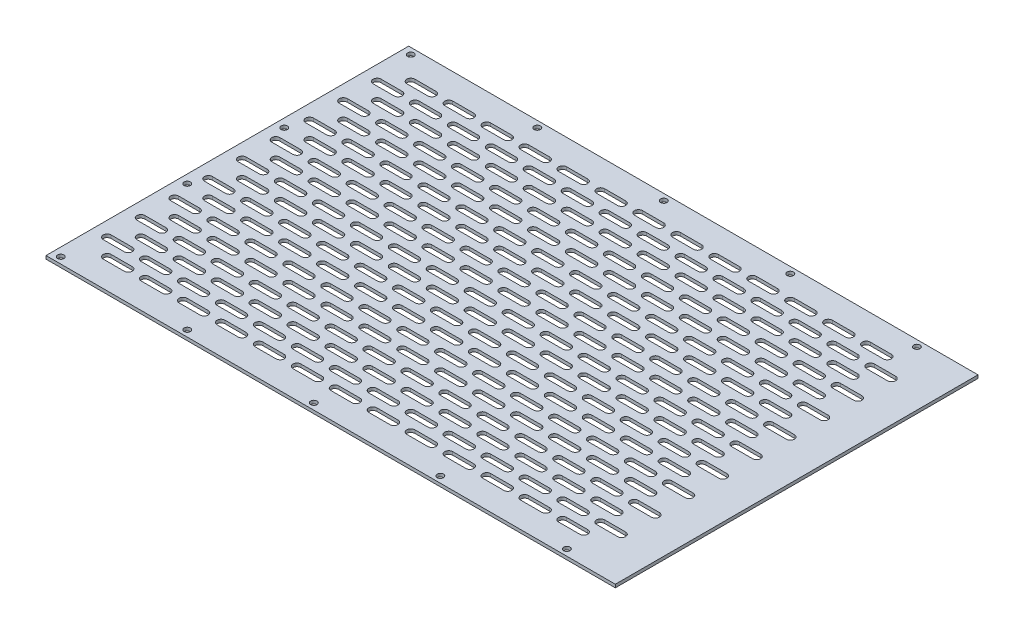
SolidWorks part; units mm, degrees
ref_plane "Front Plane" through (0, 0, 0) normal (0, 0, 1) x (1, 0, 0)
ref_plane "Top Plane" through (0, 0, 0) normal (0, 1, 0) x (1, 0, 0)
ref_plane "Right Plane" through (0, 0, 0) normal (1, 0, 0) x (0, 0, -1)
sketch "Sketch1" plane through (0, 0, 0) normal (0, 1, 0) x (1, 0, 0)
  line L0 (-120, 72) -> (-110, 72) construction
  line L1 (-135, -86) -> (135, -86)
  line L2 (-135, -86) -> (-135, 86)
  line L3 (-135, 86) -> (135, 86)
  line L4 (135, -86) -> (135, 86)
  line L5 (-135, -86) -> (135, 86) construction
  line L6 (-135, 86) -> (135, -86) construction
  line L7 (-120, 73.9) -> (-110, 73.9)
  line L8 (-120, 70.1) -> (-110, 70.1)
  line L9 (-102, 72) -> (-92, 72) construction
  line L10 (-102, 73.9) -> (-92, 73.9)
  line L11 (-102, 70.1) -> (-92, 70.1)
  line L12 (-84, 72) -> (-74, 72) construction
  line L13 (-84, 73.9) -> (-74, 73.9)
  line L14 (-84, 70.1) -> (-74, 70.1)
  line L15 (-66, 72) -> (-56, 72) construction
  line L16 (-66, 73.9) -> (-56, 73.9)
  line L17 (-66, 70.1) -> (-56, 70.1)
  line L18 (-48, 72) -> (-38, 72) construction
  line L19 (-48, 73.9) -> (-38, 73.9)
  line L20 (-48, 70.1) -> (-38, 70.1)
  line L21 (-30, 72) -> (-20, 72) construction
  line L22 (-30, 73.9) -> (-20, 73.9)
  line L23 (-30, 70.1) -> (-20, 70.1)
  line L24 (-12, 72) -> (-2, 72) construction
  line L25 (-12, 73.9) -> (-2, 73.9)
  line L26 (-12, 70.1) -> (-2, 70.1)
  line L27 (6, 72) -> (16, 72) construction
  line L28 (6, 73.9) -> (16, 73.9)
  line L29 (6, 70.1) -> (16, 70.1)
  line L30 (24, 72) -> (34, 72) construction
  line L31 (24, 73.9) -> (34, 73.9)
  line L32 (24, 70.1) -> (34, 70.1)
  line L33 (42, 72) -> (52, 72) construction
  line L34 (42, 73.9) -> (52, 73.9)
  line L35 (42, 70.1) -> (52, 70.1)
  line L36 (60, 72) -> (70, 72) construction
  line L37 (60, 73.9) -> (70, 73.9)
  line L38 (60, 70.1) -> (70, 70.1)
  line L39 (78, 72) -> (88, 72) construction
  line L40 (78, 73.9) -> (88, 73.9)
  line L41 (78, 70.1) -> (88, 70.1)
  line L42 (96, 72) -> (106, 72) construction
  line L45 (96, 73.9) -> (106, 73.9)
  line L48 (-102, 56) -> (-92, 56) construction
  line L49 (-102, 57.9) -> (-92, 57.9)
  line L50 (-102, 54.1) -> (-92, 54.1)
  line L51 (-84, 56) -> (-74, 56) construction
  line L52 (-84, 57.9) -> (-74, 57.9)
  line L53 (-84, 54.1) -> (-74, 54.1)
  line L54 (-66, 56) -> (-56, 56) construction
  line L55 (-66, 57.9) -> (-56, 57.9)
  line L56 (-66, 54.1) -> (-56, 54.1)
  line L57 (-48, 56) -> (-38, 56) construction
  line L58 (-48, 57.9) -> (-38, 57.9)
  line L59 (-48, 54.1) -> (-38, 54.1)
  line L60 (-30, 56) -> (-20, 56) construction
  line L61 (-30, 57.9) -> (-20, 57.9)
  line L62 (-30, 54.1) -> (-20, 54.1)
  line L63 (-12, 56) -> (-2, 56) construction
  line L64 (-12, 57.9) -> (-2, 57.9)
  line L65 (-12, 54.1) -> (-2, 54.1)
  line L66 (6, 56) -> (16, 56) construction
  line L67 (6, 57.9) -> (16, 57.9)
  line L68 (6, 54.1) -> (16, 54.1)
  line L69 (24, 56) -> (34, 56) construction
  line L70 (24, 57.9) -> (34, 57.9)
  line L71 (24, 54.1) -> (34, 54.1)
  line L72 (42, 56) -> (52, 56) construction
  line L73 (42, 57.9) -> (52, 57.9)
  line L74 (42, 54.1) -> (52, 54.1)
  line L75 (60, 56) -> (70, 56) construction
  line L76 (60, 57.9) -> (70, 57.9)
  line L77 (60, 54.1) -> (70, 54.1)
  line L78 (78, 56) -> (88, 56) construction
  line L79 (78, 57.9) -> (88, 57.9)
  line L80 (78, 54.1) -> (88, 54.1)
  line L81 (96, 70.1) -> (106, 70.1)
  line L84 (96, 56) -> (106, 56) construction
  line L87 (-102, 40) -> (-92, 40) construction
  line L88 (-102, 41.9) -> (-92, 41.9)
  line L89 (-102, 38.1) -> (-92, 38.1)
  line L90 (-84, 40) -> (-74, 40) construction
  line L91 (-84, 41.9) -> (-74, 41.9)
  line L92 (-84, 38.1) -> (-74, 38.1)
  line L93 (-66, 40) -> (-56, 40) construction
  line L94 (-66, 41.9) -> (-56, 41.9)
  line L95 (-66, 38.1) -> (-56, 38.1)
  line L96 (-48, 40) -> (-38, 40) construction
  line L97 (-48, 41.9) -> (-38, 41.9)
  line L98 (-48, 38.1) -> (-38, 38.1)
  line L99 (-30, 40) -> (-20, 40) construction
  line L100 (-30, 41.9) -> (-20, 41.9)
  line L101 (-30, 38.1) -> (-20, 38.1)
  line L102 (-12, 40) -> (-2, 40) construction
  line L103 (-12, 41.9) -> (-2, 41.9)
  line L104 (-12, 38.1) -> (-2, 38.1)
  line L105 (6, 40) -> (16, 40) construction
  line L106 (6, 41.9) -> (16, 41.9)
  line L107 (6, 38.1) -> (16, 38.1)
  line L108 (24, 40) -> (34, 40) construction
  line L109 (24, 41.9) -> (34, 41.9)
  line L110 (24, 38.1) -> (34, 38.1)
  line L111 (42, 40) -> (52, 40) construction
  line L112 (42, 41.9) -> (52, 41.9)
  line L113 (42, 38.1) -> (52, 38.1)
  line L114 (60, 40) -> (70, 40) construction
  line L115 (60, 41.9) -> (70, 41.9)
  line L116 (60, 38.1) -> (70, 38.1)
  line L117 (78, 40) -> (88, 40) construction
  line L118 (78, 41.9) -> (88, 41.9)
  line L119 (78, 38.1) -> (88, 38.1)
  line L120 (96, 57.9) -> (106, 57.9)
  line L123 (96, 54.1) -> (106, 54.1)
  line L126 (-102, 24) -> (-92, 24) construction
  line L127 (-102, 25.9) -> (-92, 25.9)
  line L128 (-102, 22.1) -> (-92, 22.1)
  line L129 (-84, 24) -> (-74, 24) construction
  line L130 (-84, 25.9) -> (-74, 25.9)
  line L131 (-84, 22.1) -> (-74, 22.1)
  line L132 (-66, 24) -> (-56, 24) construction
  line L133 (-66, 25.9) -> (-56, 25.9)
  line L134 (-66, 22.1) -> (-56, 22.1)
  line L135 (-48, 24) -> (-38, 24) construction
  line L136 (-48, 25.9) -> (-38, 25.9)
  line L137 (-48, 22.1) -> (-38, 22.1)
  line L138 (-30, 24) -> (-20, 24) construction
  line L139 (-30, 25.9) -> (-20, 25.9)
  line L140 (-30, 22.1) -> (-20, 22.1)
  line L141 (-12, 24) -> (-2, 24) construction
  line L142 (-12, 25.9) -> (-2, 25.9)
  line L143 (-12, 22.1) -> (-2, 22.1)
  line L144 (6, 24) -> (16, 24) construction
  line L145 (6, 25.9) -> (16, 25.9)
  line L146 (6, 22.1) -> (16, 22.1)
  line L147 (24, 24) -> (34, 24) construction
  line L148 (24, 25.9) -> (34, 25.9)
  line L149 (24, 22.1) -> (34, 22.1)
  line L150 (42, 24) -> (52, 24) construction
  line L151 (42, 25.9) -> (52, 25.9)
  line L152 (42, 22.1) -> (52, 22.1)
  line L153 (60, 24) -> (70, 24) construction
  line L154 (60, 25.9) -> (70, 25.9)
  line L155 (60, 22.1) -> (70, 22.1)
  line L156 (78, 24) -> (88, 24) construction
  line L157 (78, 25.9) -> (88, 25.9)
  line L158 (78, 22.1) -> (88, 22.1)
  line L159 (96, 40) -> (106, 40) construction
  line L162 (96, 41.9) -> (106, 41.9)
  line L165 (-102, 8) -> (-92, 8) construction
  line L166 (-102, 9.9) -> (-92, 9.9)
  line L167 (-102, 6.1) -> (-92, 6.1)
  line L168 (-84, 8) -> (-74, 8) construction
  line L169 (-84, 9.9) -> (-74, 9.9)
  line L170 (-84, 6.1) -> (-74, 6.1)
  line L171 (-66, 8) -> (-56, 8) construction
  line L172 (-66, 9.9) -> (-56, 9.9)
  line L173 (-66, 6.1) -> (-56, 6.1)
  line L174 (-48, 8) -> (-38, 8) construction
  line L175 (-48, 9.9) -> (-38, 9.9)
  line L176 (-48, 6.1) -> (-38, 6.1)
  line L177 (-30, 8) -> (-20, 8) construction
  line L178 (-30, 9.9) -> (-20, 9.9)
  line L179 (-30, 6.1) -> (-20, 6.1)
  line L180 (-12, 8) -> (-2, 8) construction
  line L181 (-12, 9.9) -> (-2, 9.9)
  line L182 (-12, 6.1) -> (-2, 6.1)
  line L183 (6, 8) -> (16, 8) construction
  line L184 (6, 9.9) -> (16, 9.9)
  line L185 (6, 6.1) -> (16, 6.1)
  line L186 (24, 8) -> (34, 8) construction
  line L187 (24, 9.9) -> (34, 9.9)
  line L188 (24, 6.1) -> (34, 6.1)
  line L189 (42, 8) -> (52, 8) construction
  line L190 (42, 9.9) -> (52, 9.9)
  line L191 (42, 6.1) -> (52, 6.1)
  line L192 (60, 8) -> (70, 8) construction
  line L193 (60, 9.9) -> (70, 9.9)
  line L194 (60, 6.1) -> (70, 6.1)
  line L195 (78, 8) -> (88, 8) construction
  line L196 (78, 9.9) -> (88, 9.9)
  line L197 (78, 6.1) -> (88, 6.1)
  line L198 (96, 38.1) -> (106, 38.1)
  line L201 (96, 24) -> (106, 24) construction
  line L204 (-102, -8) -> (-92, -8) construction
  line L205 (-102, -6.1) -> (-92, -6.1)
  line L206 (-102, -9.9) -> (-92, -9.9)
  line L207 (-84, -8) -> (-74, -8) construction
  line L208 (-84, -6.1) -> (-74, -6.1)
  line L209 (-84, -9.9) -> (-74, -9.9)
  line L210 (-66, -8) -> (-56, -8) construction
  line L211 (-66, -6.1) -> (-56, -6.1)
  line L212 (-66, -9.9) -> (-56, -9.9)
  line L213 (-48, -8) -> (-38, -8) construction
  line L214 (-48, -6.1) -> (-38, -6.1)
  line L215 (-48, -9.9) -> (-38, -9.9)
  line L216 (-30, -8) -> (-20, -8) construction
  line L217 (-30, -6.1) -> (-20, -6.1)
  line L218 (-30, -9.9) -> (-20, -9.9)
  line L219 (-12, -8) -> (-2, -8) construction
  line L220 (-12, -6.1) -> (-2, -6.1)
  line L221 (-12, -9.9) -> (-2, -9.9)
  line L222 (6, -8) -> (16, -8) construction
  line L223 (6, -6.1) -> (16, -6.1)
  line L224 (6, -9.9) -> (16, -9.9)
  line L225 (24, -8) -> (34, -8) construction
  line L226 (24, -6.1) -> (34, -6.1)
  line L227 (24, -9.9) -> (34, -9.9)
  line L228 (42, -8) -> (52, -8) construction
  line L229 (42, -6.1) -> (52, -6.1)
  line L230 (42, -9.9) -> (52, -9.9)
  line L231 (60, -8) -> (70, -8) construction
  line L232 (60, -6.1) -> (70, -6.1)
  line L233 (60, -9.9) -> (70, -9.9)
  line L234 (78, -8) -> (88, -8) construction
  line L235 (78, -6.1) -> (88, -6.1)
  line L236 (78, -9.9) -> (88, -9.9)
  line L237 (96, 25.9) -> (106, 25.9)
  line L240 (96, 22.1) -> (106, 22.1)
  line L243 (-102, -24) -> (-92, -24) construction
  line L244 (-102, -22.1) -> (-92, -22.1)
  line L245 (-102, -25.9) -> (-92, -25.9)
  line L246 (-84, -24) -> (-74, -24) construction
  line L247 (-84, -22.1) -> (-74, -22.1)
  line L248 (-84, -25.9) -> (-74, -25.9)
  line L249 (-66, -24) -> (-56, -24) construction
  line L250 (-66, -22.1) -> (-56, -22.1)
  line L251 (-66, -25.9) -> (-56, -25.9)
  line L252 (-48, -24) -> (-38, -24) construction
  line L253 (-48, -22.1) -> (-38, -22.1)
  line L254 (-48, -25.9) -> (-38, -25.9)
  line L255 (-30, -24) -> (-20, -24) construction
  line L256 (-30, -22.1) -> (-20, -22.1)
  line L257 (-30, -25.9) -> (-20, -25.9)
  line L258 (-12, -24) -> (-2, -24) construction
  line L259 (-12, -22.1) -> (-2, -22.1)
  line L260 (-12, -25.9) -> (-2, -25.9)
  line L261 (6, -24) -> (16, -24) construction
  line L262 (6, -22.1) -> (16, -22.1)
  line L263 (6, -25.9) -> (16, -25.9)
  line L264 (24, -24) -> (34, -24) construction
  line L265 (24, -22.1) -> (34, -22.1)
  line L266 (24, -25.9) -> (34, -25.9)
  line L267 (42, -24) -> (52, -24) construction
  line L268 (42, -22.1) -> (52, -22.1)
  line L269 (42, -25.9) -> (52, -25.9)
  line L270 (60, -24) -> (70, -24) construction
  line L271 (60, -22.1) -> (70, -22.1)
  line L272 (60, -25.9) -> (70, -25.9)
  line L273 (78, -24) -> (88, -24) construction
  line L274 (78, -22.1) -> (88, -22.1)
  line L275 (78, -25.9) -> (88, -25.9)
  line L276 (96, 8) -> (106, 8) construction
  line L279 (96, 9.9) -> (106, 9.9)
  line L282 (-102, -40) -> (-92, -40) construction
  line L283 (-102, -38.1) -> (-92, -38.1)
  line L284 (-102, -41.9) -> (-92, -41.9)
  line L285 (-84, -40) -> (-74, -40) construction
  line L286 (-84, -38.1) -> (-74, -38.1)
  line L287 (-84, -41.9) -> (-74, -41.9)
  line L288 (-66, -40) -> (-56, -40) construction
  line L289 (-66, -38.1) -> (-56, -38.1)
  line L290 (-66, -41.9) -> (-56, -41.9)
  line L291 (-48, -40) -> (-38, -40) construction
  line L292 (-48, -38.1) -> (-38, -38.1)
  line L293 (-48, -41.9) -> (-38, -41.9)
  line L294 (-30, -40) -> (-20, -40) construction
  line L295 (-30, -38.1) -> (-20, -38.1)
  line L296 (-30, -41.9) -> (-20, -41.9)
  line L297 (-12, -40) -> (-2, -40) construction
  line L298 (-12, -38.1) -> (-2, -38.1)
  line L299 (-12, -41.9) -> (-2, -41.9)
  line L300 (6, -40) -> (16, -40) construction
  line L301 (6, -38.1) -> (16, -38.1)
  line L302 (6, -41.9) -> (16, -41.9)
  line L303 (24, -40) -> (34, -40) construction
  line L304 (24, -38.1) -> (34, -38.1)
  line L305 (24, -41.9) -> (34, -41.9)
  line L306 (42, -40) -> (52, -40) construction
  line L307 (42, -38.1) -> (52, -38.1)
  line L308 (42, -41.9) -> (52, -41.9)
  line L309 (60, -40) -> (70, -40) construction
  line L310 (60, -38.1) -> (70, -38.1)
  line L311 (60, -41.9) -> (70, -41.9)
  line L312 (78, -40) -> (88, -40) construction
  line L313 (78, -38.1) -> (88, -38.1)
  line L314 (78, -41.9) -> (88, -41.9)
  line L315 (96, 6.1) -> (106, 6.1)
  line L318 (96, -8) -> (106, -8) construction
  line L321 (-102, -56) -> (-92, -56) construction
  line L322 (-102, -54.1) -> (-92, -54.1)
  line L323 (-102, -57.9) -> (-92, -57.9)
  line L324 (-84, -56) -> (-74, -56) construction
  line L325 (-84, -54.1) -> (-74, -54.1)
  line L326 (-84, -57.9) -> (-74, -57.9)
  line L327 (-66, -56) -> (-56, -56) construction
  line L328 (-66, -54.1) -> (-56, -54.1)
  line L329 (-66, -57.9) -> (-56, -57.9)
  line L330 (-48, -56) -> (-38, -56) construction
  line L331 (-48, -54.1) -> (-38, -54.1)
  line L332 (-48, -57.9) -> (-38, -57.9)
  line L333 (-30, -56) -> (-20, -56) construction
  line L334 (-30, -54.1) -> (-20, -54.1)
  line L335 (-30, -57.9) -> (-20, -57.9)
  line L336 (-12, -56) -> (-2, -56) construction
  line L337 (-12, -54.1) -> (-2, -54.1)
  line L338 (-12, -57.9) -> (-2, -57.9)
  line L339 (6, -56) -> (16, -56) construction
  line L340 (6, -54.1) -> (16, -54.1)
  line L341 (6, -57.9) -> (16, -57.9)
  line L342 (24, -56) -> (34, -56) construction
  line L343 (24, -54.1) -> (34, -54.1)
  line L344 (24, -57.9) -> (34, -57.9)
  line L345 (42, -56) -> (52, -56) construction
  line L346 (42, -54.1) -> (52, -54.1)
  line L347 (42, -57.9) -> (52, -57.9)
  line L348 (60, -56) -> (70, -56) construction
  line L349 (60, -54.1) -> (70, -54.1)
  line L350 (60, -57.9) -> (70, -57.9)
  line L351 (78, -56) -> (88, -56) construction
  line L352 (78, -54.1) -> (88, -54.1)
  line L353 (78, -57.9) -> (88, -57.9)
  line L354 (96, -6.1) -> (106, -6.1)
  line L357 (96, -9.9) -> (106, -9.9)
  line L360 (-102, -72) -> (-92, -72) construction
  line L361 (-102, -70.1) -> (-92, -70.1)
  line L362 (-102, -73.9) -> (-92, -73.9)
  line L363 (-84, -72) -> (-74, -72) construction
  line L364 (-84, -70.1) -> (-74, -70.1)
  line L365 (-84, -73.9) -> (-74, -73.9)
  line L366 (-66, -72) -> (-56, -72) construction
  line L367 (-66, -70.1) -> (-56, -70.1)
  line L368 (-66, -73.9) -> (-56, -73.9)
  line L369 (-48, -72) -> (-38, -72) construction
  line L370 (-48, -70.1) -> (-38, -70.1)
  line L371 (-48, -73.9) -> (-38, -73.9)
  line L372 (-30, -72) -> (-20, -72) construction
  line L373 (-30, -70.1) -> (-20, -70.1)
  line L374 (-30, -73.9) -> (-20, -73.9)
  line L375 (-12, -72) -> (-2, -72) construction
  line L376 (-12, -70.1) -> (-2, -70.1)
  line L377 (-12, -73.9) -> (-2, -73.9)
  line L378 (6, -72) -> (16, -72) construction
  line L379 (6, -70.1) -> (16, -70.1)
  line L380 (6, -73.9) -> (16, -73.9)
  line L381 (24, -72) -> (34, -72) construction
  line L382 (24, -70.1) -> (34, -70.1)
  line L383 (24, -73.9) -> (34, -73.9)
  line L384 (42, -72) -> (52, -72) construction
  line L385 (42, -70.1) -> (52, -70.1)
  line L386 (42, -73.9) -> (52, -73.9)
  line L387 (60, -72) -> (70, -72) construction
  line L388 (60, -70.1) -> (70, -70.1)
  line L389 (60, -73.9) -> (70, -73.9)
  line L390 (78, -72) -> (88, -72) construction
  line L391 (78, -70.1) -> (88, -70.1)
  line L392 (78, -73.9) -> (88, -73.9)
  line L393 (96, -24) -> (106, -24) construction
  line L396 (96, -22.1) -> (106, -22.1)
  line L399 (-120, 56) -> (-110, 56) construction
  line L400 (-120, 57.9) -> (-110, 57.9)
  line L401 (-120, 54.1) -> (-110, 54.1)
  line L402 (-120, 40) -> (-110, 40) construction
  line L403 (-120, 41.9) -> (-110, 41.9)
  line L404 (-120, 38.1) -> (-110, 38.1)
  line L405 (-120, 24) -> (-110, 24) construction
  line L406 (-120, 25.9) -> (-110, 25.9)
  line L407 (-120, 22.1) -> (-110, 22.1)
  line L408 (-120, 8) -> (-110, 8) construction
  line L409 (-120, 9.9) -> (-110, 9.9)
  line L410 (-120, 6.1) -> (-110, 6.1)
  line L411 (-120, -8) -> (-110, -8) construction
  line L412 (-120, -6.1) -> (-110, -6.1)
  line L413 (-120, -9.9) -> (-110, -9.9)
  line L414 (-120, -24) -> (-110, -24) construction
  line L415 (-120, -22.1) -> (-110, -22.1)
  line L416 (-120, -25.9) -> (-110, -25.9)
  line L417 (-120, -40) -> (-110, -40) construction
  line L418 (-120, -38.1) -> (-110, -38.1)
  line L419 (-120, -41.9) -> (-110, -41.9)
  line L420 (-120, -56) -> (-110, -56) construction
  line L421 (-120, -54.1) -> (-110, -54.1)
  line L422 (-120, -57.9) -> (-110, -57.9)
  line L423 (-120, -72) -> (-110, -72) construction
  line L424 (-120, -70.1) -> (-110, -70.1)
  line L425 (-120, -73.9) -> (-110, -73.9)
  line L426 (-110, 64) -> (-100, 64) construction
  line L427 (-110, 65.9) -> (-100, 65.9)
  line L428 (-110, 62.1) -> (-100, 62.1)
  line L429 (-92, 64) -> (-82, 64) construction
  line L430 (-92, 65.9) -> (-82, 65.9)
  line L431 (-92, 62.1) -> (-82, 62.1)
  line L432 (-74, 64) -> (-64, 64) construction
  line L433 (-74, 65.9) -> (-64, 65.9)
  line L434 (-74, 62.1) -> (-64, 62.1)
  line L435 (-56, 64) -> (-46, 64) construction
  line L436 (-56, 65.9) -> (-46, 65.9)
  line L437 (-56, 62.1) -> (-46, 62.1)
  line L438 (-38, 64) -> (-28, 64) construction
  line L439 (-38, 65.9) -> (-28, 65.9)
  line L440 (-38, 62.1) -> (-28, 62.1)
  line L441 (-20, 64) -> (-10, 64) construction
  line L442 (-20, 65.9) -> (-10, 65.9)
  line L443 (-20, 62.1) -> (-10, 62.1)
  line L444 (-2, 64) -> (8, 64) construction
  line L445 (-2, 65.9) -> (8, 65.9)
  line L446 (-2, 62.1) -> (8, 62.1)
  line L447 (16, 64) -> (26, 64) construction
  line L448 (16, 65.9) -> (26, 65.9)
  line L449 (16, 62.1) -> (26, 62.1)
  line L450 (34, 64) -> (44, 64) construction
  line L451 (34, 65.9) -> (44, 65.9)
  line L452 (34, 62.1) -> (44, 62.1)
  line L453 (52, 64) -> (62, 64) construction
  line L454 (52, 65.9) -> (62, 65.9)
  line L455 (52, 62.1) -> (62, 62.1)
  line L456 (70, 64) -> (80, 64) construction
  line L457 (70, 65.9) -> (80, 65.9)
  line L458 (70, 62.1) -> (80, 62.1)
  line L459 (88, 64) -> (98, 64) construction
  line L460 (88, 65.9) -> (98, 65.9)
  line L461 (88, 62.1) -> (98, 62.1)
  line L462 (96, -25.9) -> (106, -25.9)
  line L465 (96, -40) -> (106, -40) construction
  line L468 (-92, 48) -> (-82, 48) construction
  line L469 (-92, 49.9) -> (-82, 49.9)
  line L470 (-92, 46.1) -> (-82, 46.1)
  line L471 (-74, 48) -> (-64, 48) construction
  line L472 (-74, 49.9) -> (-64, 49.9)
  line L473 (-74, 46.1) -> (-64, 46.1)
  line L474 (-56, 48) -> (-46, 48) construction
  line L475 (-56, 49.9) -> (-46, 49.9)
  line L476 (-56, 46.1) -> (-46, 46.1)
  line L477 (-38, 48) -> (-28, 48) construction
  line L478 (-38, 49.9) -> (-28, 49.9)
  line L479 (-38, 46.1) -> (-28, 46.1)
  line L480 (-20, 48) -> (-10, 48) construction
  line L481 (-20, 49.9) -> (-10, 49.9)
  line L482 (-20, 46.1) -> (-10, 46.1)
  line L483 (-2, 48) -> (8, 48) construction
  line L484 (-2, 49.9) -> (8, 49.9)
  line L485 (-2, 46.1) -> (8, 46.1)
  line L486 (16, 48) -> (26, 48) construction
  line L487 (16, 49.9) -> (26, 49.9)
  line L488 (16, 46.1) -> (26, 46.1)
  line L489 (34, 48) -> (44, 48) construction
  line L490 (34, 49.9) -> (44, 49.9)
  line L491 (34, 46.1) -> (44, 46.1)
  line L492 (52, 48) -> (62, 48) construction
  line L493 (52, 49.9) -> (62, 49.9)
  line L494 (52, 46.1) -> (62, 46.1)
  line L495 (70, 48) -> (80, 48) construction
  line L496 (70, 49.9) -> (80, 49.9)
  line L497 (70, 46.1) -> (80, 46.1)
  line L498 (88, 48) -> (98, 48) construction
  line L499 (88, 49.9) -> (98, 49.9)
  line L500 (88, 46.1) -> (98, 46.1)
  line L501 (96, -38.1) -> (106, -38.1)
  line L504 (96, -41.9) -> (106, -41.9)
  line L507 (-92, 32) -> (-82, 32) construction
  line L508 (-92, 33.9) -> (-82, 33.9)
  line L509 (-92, 30.1) -> (-82, 30.1)
  line L510 (-74, 32) -> (-64, 32) construction
  line L511 (-74, 33.9) -> (-64, 33.9)
  line L512 (-74, 30.1) -> (-64, 30.1)
  line L513 (-56, 32) -> (-46, 32) construction
  line L514 (-56, 33.9) -> (-46, 33.9)
  line L515 (-56, 30.1) -> (-46, 30.1)
  line L516 (-38, 32) -> (-28, 32) construction
  line L517 (-38, 33.9) -> (-28, 33.9)
  line L518 (-38, 30.1) -> (-28, 30.1)
  line L519 (-20, 32) -> (-10, 32) construction
  line L520 (-20, 33.9) -> (-10, 33.9)
  line L521 (-20, 30.1) -> (-10, 30.1)
  line L522 (-2, 32) -> (8, 32) construction
  line L523 (-2, 33.9) -> (8, 33.9)
  line L524 (-2, 30.1) -> (8, 30.1)
  line L525 (16, 32) -> (26, 32) construction
  line L526 (16, 33.9) -> (26, 33.9)
  line L527 (16, 30.1) -> (26, 30.1)
  line L528 (34, 32) -> (44, 32) construction
  line L529 (34, 33.9) -> (44, 33.9)
  line L530 (34, 30.1) -> (44, 30.1)
  line L531 (52, 32) -> (62, 32) construction
  line L532 (52, 33.9) -> (62, 33.9)
  line L533 (52, 30.1) -> (62, 30.1)
  line L534 (70, 32) -> (80, 32) construction
  line L535 (70, 33.9) -> (80, 33.9)
  line L536 (70, 30.1) -> (80, 30.1)
  line L537 (88, 32) -> (98, 32) construction
  line L538 (88, 33.9) -> (98, 33.9)
  line L539 (88, 30.1) -> (98, 30.1)
  line L540 (96, -56) -> (106, -56) construction
  line L543 (96, -54.1) -> (106, -54.1)
  line L546 (-92, 16) -> (-82, 16) construction
  line L547 (-92, 17.9) -> (-82, 17.9)
  line L548 (-92, 14.1) -> (-82, 14.1)
  line L549 (-74, 16) -> (-64, 16) construction
  line L550 (-74, 17.9) -> (-64, 17.9)
  line L551 (-74, 14.1) -> (-64, 14.1)
  line L552 (-56, 16) -> (-46, 16) construction
  line L553 (-56, 17.9) -> (-46, 17.9)
  line L554 (-56, 14.1) -> (-46, 14.1)
  line L555 (-38, 16) -> (-28, 16) construction
  line L556 (-38, 17.9) -> (-28, 17.9)
  line L557 (-38, 14.1) -> (-28, 14.1)
  line L558 (-20, 16) -> (-10, 16) construction
  line L559 (-20, 17.9) -> (-10, 17.9)
  line L560 (-20, 14.1) -> (-10, 14.1)
  line L561 (-2, 16) -> (8, 16) construction
  line L562 (-2, 17.9) -> (8, 17.9)
  line L563 (-2, 14.1) -> (8, 14.1)
  line L564 (16, 16) -> (26, 16) construction
  line L565 (16, 17.9) -> (26, 17.9)
  line L566 (16, 14.1) -> (26, 14.1)
  line L567 (34, 16) -> (44, 16) construction
  line L568 (34, 17.9) -> (44, 17.9)
  line L569 (34, 14.1) -> (44, 14.1)
  line L570 (52, 16) -> (62, 16) construction
  line L571 (52, 17.9) -> (62, 17.9)
  line L572 (52, 14.1) -> (62, 14.1)
  line L573 (70, 16) -> (80, 16) construction
  line L574 (70, 17.9) -> (80, 17.9)
  line L575 (70, 14.1) -> (80, 14.1)
  line L576 (88, 16) -> (98, 16) construction
  line L577 (88, 17.9) -> (98, 17.9)
  line L578 (88, 14.1) -> (98, 14.1)
  line L579 (96, -57.9) -> (106, -57.9)
  line L582 (96, -72) -> (106, -72) construction
  line L585 (-92, 0) -> (-82, 0) construction
  line L586 (-92, 1.9) -> (-82, 1.9)
  line L587 (-92, -1.9) -> (-82, -1.9)
  line L588 (-74, 0) -> (-64, 0) construction
  line L589 (-74, 1.9) -> (-64, 1.9)
  line L590 (-74, -1.9) -> (-64, -1.9)
  line L591 (-56, 0) -> (-46, 0) construction
  line L592 (-56, 1.9) -> (-46, 1.9)
  line L593 (-56, -1.9) -> (-46, -1.9)
  line L594 (-38, 0) -> (-28, 0) construction
  line L595 (-38, 1.9) -> (-28, 1.9)
  line L596 (-38, -1.9) -> (-28, -1.9)
  line L597 (-20, 0) -> (-10, 0) construction
  line L598 (-20, 1.9) -> (-10, 1.9)
  line L599 (-20, -1.9) -> (-10, -1.9)
  line L600 (-2, 0) -> (8, 0) construction
  line L601 (-2, 1.9) -> (8, 1.9)
  line L602 (-2, -1.9) -> (8, -1.9)
  line L603 (16, 0) -> (26, 0) construction
  line L604 (16, 1.9) -> (26, 1.9)
  line L605 (16, -1.9) -> (26, -1.9)
  line L606 (34, 0) -> (44, 0) construction
  line L607 (34, 1.9) -> (44, 1.9)
  line L608 (34, -1.9) -> (44, -1.9)
  line L609 (52, 0) -> (62, 0) construction
  line L610 (52, 1.9) -> (62, 1.9)
  line L611 (52, -1.9) -> (62, -1.9)
  line L612 (70, 0) -> (80, 0) construction
  line L613 (70, 1.9) -> (80, 1.9)
  line L614 (70, -1.9) -> (80, -1.9)
  line L615 (88, 0) -> (98, 0) construction
  line L616 (88, 1.9) -> (98, 1.9)
  line L617 (88, -1.9) -> (98, -1.9)
  line L618 (96, -70.1) -> (106, -70.1)
  line L621 (96, -73.9) -> (106, -73.9)
  line L624 (-92, -16) -> (-82, -16) construction
  line L625 (-92, -14.1) -> (-82, -14.1)
  line L626 (-92, -17.9) -> (-82, -17.9)
  line L627 (-74, -16) -> (-64, -16) construction
  line L628 (-74, -14.1) -> (-64, -14.1)
  line L629 (-74, -17.9) -> (-64, -17.9)
  line L630 (-56, -16) -> (-46, -16) construction
  line L631 (-56, -14.1) -> (-46, -14.1)
  line L632 (-56, -17.9) -> (-46, -17.9)
  line L633 (-38, -16) -> (-28, -16) construction
  line L634 (-38, -14.1) -> (-28, -14.1)
  line L635 (-38, -17.9) -> (-28, -17.9)
  line L636 (-20, -16) -> (-10, -16) construction
  line L637 (-20, -14.1) -> (-10, -14.1)
  line L638 (-20, -17.9) -> (-10, -17.9)
  line L639 (-2, -16) -> (8, -16) construction
  line L640 (-2, -14.1) -> (8, -14.1)
  line L641 (-2, -17.9) -> (8, -17.9)
  line L642 (16, -16) -> (26, -16) construction
  line L643 (16, -14.1) -> (26, -14.1)
  line L644 (16, -17.9) -> (26, -17.9)
  line L645 (34, -16) -> (44, -16) construction
  line L646 (34, -14.1) -> (44, -14.1)
  line L647 (34, -17.9) -> (44, -17.9)
  line L648 (52, -16) -> (62, -16) construction
  line L649 (52, -14.1) -> (62, -14.1)
  line L650 (52, -17.9) -> (62, -17.9)
  line L651 (70, -16) -> (80, -16) construction
  line L652 (70, -14.1) -> (80, -14.1)
  line L653 (70, -17.9) -> (80, -17.9)
  line L654 (88, -16) -> (98, -16) construction
  line L655 (88, -14.1) -> (98, -14.1)
  line L656 (88, -17.9) -> (98, -17.9)
  line L657 (106, 64) -> (116, 64) construction
  line L660 (106, 65.9) -> (116, 65.9)
  line L663 (-92, -32) -> (-82, -32) construction
  line L664 (-92, -30.1) -> (-82, -30.1)
  line L665 (-92, -33.9) -> (-82, -33.9)
  line L666 (-74, -32) -> (-64, -32) construction
  line L667 (-74, -30.1) -> (-64, -30.1)
  line L668 (-74, -33.9) -> (-64, -33.9)
  line L669 (-56, -32) -> (-46, -32) construction
  line L670 (-56, -30.1) -> (-46, -30.1)
  line L671 (-56, -33.9) -> (-46, -33.9)
  line L672 (-38, -32) -> (-28, -32) construction
  line L673 (-38, -30.1) -> (-28, -30.1)
  line L674 (-38, -33.9) -> (-28, -33.9)
  line L675 (-20, -32) -> (-10, -32) construction
  line L676 (-20, -30.1) -> (-10, -30.1)
  line L677 (-20, -33.9) -> (-10, -33.9)
  line L678 (-2, -32) -> (8, -32) construction
  line L679 (-2, -30.1) -> (8, -30.1)
  line L680 (-2, -33.9) -> (8, -33.9)
  line L681 (16, -32) -> (26, -32) construction
  line L682 (16, -30.1) -> (26, -30.1)
  line L683 (16, -33.9) -> (26, -33.9)
  line L684 (34, -32) -> (44, -32) construction
  line L685 (34, -30.1) -> (44, -30.1)
  line L686 (34, -33.9) -> (44, -33.9)
  line L687 (52, -32) -> (62, -32) construction
  line L688 (52, -30.1) -> (62, -30.1)
  line L689 (52, -33.9) -> (62, -33.9)
  line L690 (70, -32) -> (80, -32) construction
  line L691 (70, -30.1) -> (80, -30.1)
  line L692 (70, -33.9) -> (80, -33.9)
  line L693 (88, -32) -> (98, -32) construction
  line L694 (88, -30.1) -> (98, -30.1)
  line L695 (88, -33.9) -> (98, -33.9)
  line L696 (106, 62.1) -> (116, 62.1)
  line L699 (106, 48) -> (116, 48) construction
  line L702 (-92, -48) -> (-82, -48) construction
  line L703 (-92, -46.1) -> (-82, -46.1)
  line L704 (-92, -49.9) -> (-82, -49.9)
  line L705 (-74, -48) -> (-64, -48) construction
  line L706 (-74, -46.1) -> (-64, -46.1)
  line L707 (-74, -49.9) -> (-64, -49.9)
  line L708 (-56, -48) -> (-46, -48) construction
  line L709 (-56, -46.1) -> (-46, -46.1)
  line L710 (-56, -49.9) -> (-46, -49.9)
  line L711 (-38, -48) -> (-28, -48) construction
  line L712 (-38, -46.1) -> (-28, -46.1)
  line L713 (-38, -49.9) -> (-28, -49.9)
  line L714 (-20, -48) -> (-10, -48) construction
  line L715 (-20, -46.1) -> (-10, -46.1)
  line L716 (-20, -49.9) -> (-10, -49.9)
  line L717 (-2, -48) -> (8, -48) construction
  line L718 (-2, -46.1) -> (8, -46.1)
  line L719 (-2, -49.9) -> (8, -49.9)
  line L720 (16, -48) -> (26, -48) construction
  line L721 (16, -46.1) -> (26, -46.1)
  line L722 (16, -49.9) -> (26, -49.9)
  line L723 (34, -48) -> (44, -48) construction
  line L724 (34, -46.1) -> (44, -46.1)
  line L725 (34, -49.9) -> (44, -49.9)
  line L726 (52, -48) -> (62, -48) construction
  line L727 (52, -46.1) -> (62, -46.1)
  line L728 (52, -49.9) -> (62, -49.9)
  line L729 (70, -48) -> (80, -48) construction
  line L730 (70, -46.1) -> (80, -46.1)
  line L731 (70, -49.9) -> (80, -49.9)
  line L732 (88, -48) -> (98, -48) construction
  line L733 (88, -46.1) -> (98, -46.1)
  line L734 (88, -49.9) -> (98, -49.9)
  line L735 (106, 49.9) -> (116, 49.9)
  line L738 (106, 46.1) -> (116, 46.1)
  line L741 (-92, -64) -> (-82, -64) construction
  line L742 (-92, -62.1) -> (-82, -62.1)
  line L743 (-92, -65.9) -> (-82, -65.9)
  line L744 (-74, -64) -> (-64, -64) construction
  line L745 (-74, -62.1) -> (-64, -62.1)
  line L746 (-74, -65.9) -> (-64, -65.9)
  line L747 (-56, -64) -> (-46, -64) construction
  line L748 (-56, -62.1) -> (-46, -62.1)
  line L749 (-56, -65.9) -> (-46, -65.9)
  line L750 (-38, -64) -> (-28, -64) construction
  line L751 (-38, -62.1) -> (-28, -62.1)
  line L752 (-38, -65.9) -> (-28, -65.9)
  line L753 (-20, -64) -> (-10, -64) construction
  line L754 (-20, -62.1) -> (-10, -62.1)
  line L755 (-20, -65.9) -> (-10, -65.9)
  line L756 (-2, -64) -> (8, -64) construction
  line L757 (-2, -62.1) -> (8, -62.1)
  line L758 (-2, -65.9) -> (8, -65.9)
  line L759 (16, -64) -> (26, -64) construction
  line L760 (16, -62.1) -> (26, -62.1)
  line L761 (16, -65.9) -> (26, -65.9)
  line L762 (34, -64) -> (44, -64) construction
  line L763 (34, -62.1) -> (44, -62.1)
  line L764 (34, -65.9) -> (44, -65.9)
  line L765 (52, -64) -> (62, -64) construction
  line L766 (52, -62.1) -> (62, -62.1)
  line L767 (52, -65.9) -> (62, -65.9)
  line L768 (70, -64) -> (80, -64) construction
  line L769 (70, -62.1) -> (80, -62.1)
  line L770 (70, -65.9) -> (80, -65.9)
  line L771 (88, -64) -> (98, -64) construction
  line L772 (88, -62.1) -> (98, -62.1)
  line L773 (88, -65.9) -> (98, -65.9)
  line L774 (106, 32) -> (116, 32) construction
  line L777 (106, 33.9) -> (116, 33.9)
  line L780 (-110, 48) -> (-100, 48) construction
  line L781 (-110, 49.9) -> (-100, 49.9)
  line L782 (-110, 46.1) -> (-100, 46.1)
  line L783 (-110, 32) -> (-100, 32) construction
  line L784 (-110, 33.9) -> (-100, 33.9)
  line L785 (-110, 30.1) -> (-100, 30.1)
  line L786 (-110, 16) -> (-100, 16) construction
  line L787 (-110, 17.9) -> (-100, 17.9)
  line L788 (-110, 14.1) -> (-100, 14.1)
  line L789 (-110, 0) -> (-100, 0) construction
  line L790 (-110, 1.9) -> (-100, 1.9)
  line L791 (-110, -1.9) -> (-100, -1.9)
  line L792 (-110, -16) -> (-100, -16) construction
  line L793 (-110, -14.1) -> (-100, -14.1)
  line L794 (-110, -17.9) -> (-100, -17.9)
  line L795 (-110, -32) -> (-100, -32) construction
  line L796 (-110, -30.1) -> (-100, -30.1)
  line L797 (-110, -33.9) -> (-100, -33.9)
  line L798 (-110, -48) -> (-100, -48) construction
  line L799 (-110, -46.1) -> (-100, -46.1)
  line L800 (-110, -49.9) -> (-100, -49.9)
  line L801 (-110, -64) -> (-100, -64) construction
  line L802 (-110, -62.1) -> (-100, -62.1)
  line L803 (-110, -65.9) -> (-100, -65.9)
  line L804 (-128, 64) -> (-118, 64) construction
  line L805 (-128, 65.9) -> (-118, 65.9)
  line L806 (-128, 62.1) -> (-118, 62.1)
  line L807 (-128, 48) -> (-118, 48) construction
  line L808 (-128, 49.9) -> (-118, 49.9)
  line L809 (-128, 46.1) -> (-118, 46.1)
  line L810 (-128, 32) -> (-118, 32) construction
  line L811 (-128, 33.9) -> (-118, 33.9)
  line L812 (-128, 30.1) -> (-118, 30.1)
  line L813 (-128, 16) -> (-118, 16) construction
  line L814 (-128, 17.9) -> (-118, 17.9)
  line L815 (-128, 14.1) -> (-118, 14.1)
  line L816 (-128, 0) -> (-118, 0) construction
  line L817 (-128, 1.9) -> (-118, 1.9)
  line L818 (-128, -1.9) -> (-118, -1.9)
  line L819 (-128, -16) -> (-118, -16) construction
  line L820 (-128, -14.1) -> (-118, -14.1)
  line L821 (-128, -17.9) -> (-118, -17.9)
  line L822 (-128, -32) -> (-118, -32) construction
  line L823 (-128, -30.1) -> (-118, -30.1)
  line L824 (-128, -33.9) -> (-118, -33.9)
  line L825 (-128, -48) -> (-118, -48) construction
  line L826 (-128, -46.1) -> (-118, -46.1)
  line L827 (-128, -49.9) -> (-118, -49.9)
  line L828 (-128, -64) -> (-118, -64) construction
  line L829 (-128, -62.1) -> (-118, -62.1)
  line L830 (-128, -65.9) -> (-118, -65.9)
  line L831 (0, 0) -> (7.5768, 0) construction
  line L832 (106, 30.1) -> (116, 30.1)
  line L833 (106, 16) -> (116, 16) construction
  line L834 (106, 17.9) -> (116, 17.9)
  line L835 (106, 14.1) -> (116, 14.1)
  line L836 (106, 0) -> (116, 0) construction
  line L837 (106, 1.9) -> (116, 1.9)
  line L838 (106, -1.9) -> (116, -1.9)
  line L839 (106, -16) -> (116, -16) construction
  line L840 (106, -14.1) -> (116, -14.1)
  line L841 (106, -17.9) -> (116, -17.9)
  line L842 (106, -32) -> (116, -32) construction
  line L843 (106, -30.1) -> (116, -30.1)
  line L844 (106, -33.9) -> (116, -33.9)
  line L845 (106, -48) -> (116, -48) construction
  line L846 (106, -46.1) -> (116, -46.1)
  line L847 (106, -49.9) -> (116, -49.9)
  line L848 (106, -64) -> (116, -64) construction
  line L849 (106, -62.1) -> (116, -62.1)
  line L850 (106, -65.9) -> (116, -65.9)
  arc A0 (-120, 73.9) -> (-120, 70.1) centre (-120, 72) ccw
  arc A1 (-110, 70.1) -> (-110, 73.9) centre (-110, 72) ccw
  arc A2 (-102, 73.9) -> (-102, 70.1) centre (-102, 72) ccw
  arc A3 (-92, 70.1) -> (-92, 73.9) centre (-92, 72) ccw
  arc A4 (-84, 73.9) -> (-84, 70.1) centre (-84, 72) ccw
  arc A5 (-74, 70.1) -> (-74, 73.9) centre (-74, 72) ccw
  arc A6 (-66, 73.9) -> (-66, 70.1) centre (-66, 72) ccw
  arc A7 (-56, 70.1) -> (-56, 73.9) centre (-56, 72) ccw
  arc A8 (-48, 73.9) -> (-48, 70.1) centre (-48, 72) ccw
  arc A9 (-38, 70.1) -> (-38, 73.9) centre (-38, 72) ccw
  arc A10 (-30, 73.9) -> (-30, 70.1) centre (-30, 72) ccw
  arc A11 (-20, 70.1) -> (-20, 73.9) centre (-20, 72) ccw
  arc A12 (-12, 73.9) -> (-12, 70.1) centre (-12, 72) ccw
  arc A13 (-2, 70.1) -> (-2, 73.9) centre (-2, 72) ccw
  arc A14 (6, 73.9) -> (6, 70.1) centre (6, 72) ccw
  arc A15 (16, 70.1) -> (16, 73.9) centre (16, 72) ccw
  arc A16 (24, 73.9) -> (24, 70.1) centre (24, 72) ccw
  arc A17 (34, 70.1) -> (34, 73.9) centre (34, 72) ccw
  arc A18 (42, 73.9) -> (42, 70.1) centre (42, 72) ccw
  arc A19 (52, 70.1) -> (52, 73.9) centre (52, 72) ccw
  arc A20 (60, 73.9) -> (60, 70.1) centre (60, 72) ccw
  arc A21 (70, 70.1) -> (70, 73.9) centre (70, 72) ccw
  arc A22 (78, 73.9) -> (78, 70.1) centre (78, 72) ccw
  arc A23 (88, 70.1) -> (88, 73.9) centre (88, 72) ccw
  arc A28 (-102, 57.9) -> (-102, 54.1) centre (-102, 56) ccw
  arc A29 (-92, 54.1) -> (-92, 57.9) centre (-92, 56) ccw
  arc A30 (-84, 57.9) -> (-84, 54.1) centre (-84, 56) ccw
  arc A31 (-74, 54.1) -> (-74, 57.9) centre (-74, 56) ccw
  arc A32 (-66, 57.9) -> (-66, 54.1) centre (-66, 56) ccw
  arc A33 (-56, 54.1) -> (-56, 57.9) centre (-56, 56) ccw
  arc A34 (-48, 57.9) -> (-48, 54.1) centre (-48, 56) ccw
  arc A35 (-38, 54.1) -> (-38, 57.9) centre (-38, 56) ccw
  arc A36 (-30, 57.9) -> (-30, 54.1) centre (-30, 56) ccw
  arc A37 (-20, 54.1) -> (-20, 57.9) centre (-20, 56) ccw
  arc A38 (-12, 57.9) -> (-12, 54.1) centre (-12, 56) ccw
  arc A39 (-2, 54.1) -> (-2, 57.9) centre (-2, 56) ccw
  arc A40 (6, 57.9) -> (6, 54.1) centre (6, 56) ccw
  arc A41 (16, 54.1) -> (16, 57.9) centre (16, 56) ccw
  arc A42 (24, 57.9) -> (24, 54.1) centre (24, 56) ccw
  arc A43 (34, 54.1) -> (34, 57.9) centre (34, 56) ccw
  arc A44 (42, 57.9) -> (42, 54.1) centre (42, 56) ccw
  arc A45 (52, 54.1) -> (52, 57.9) centre (52, 56) ccw
  arc A46 (60, 57.9) -> (60, 54.1) centre (60, 56) ccw
  arc A47 (70, 54.1) -> (70, 57.9) centre (70, 56) ccw
  arc A48 (78, 57.9) -> (78, 54.1) centre (78, 56) ccw
  arc A49 (88, 54.1) -> (88, 57.9) centre (88, 56) ccw
  arc A54 (-102, 41.9) -> (-102, 38.1) centre (-102, 40) ccw
  arc A55 (-92, 38.1) -> (-92, 41.9) centre (-92, 40) ccw
  arc A56 (-84, 41.9) -> (-84, 38.1) centre (-84, 40) ccw
  arc A57 (-74, 38.1) -> (-74, 41.9) centre (-74, 40) ccw
  arc A58 (-66, 41.9) -> (-66, 38.1) centre (-66, 40) ccw
  arc A59 (-56, 38.1) -> (-56, 41.9) centre (-56, 40) ccw
  arc A60 (-48, 41.9) -> (-48, 38.1) centre (-48, 40) ccw
  arc A61 (-38, 38.1) -> (-38, 41.9) centre (-38, 40) ccw
  arc A62 (-30, 41.9) -> (-30, 38.1) centre (-30, 40) ccw
  arc A63 (-20, 38.1) -> (-20, 41.9) centre (-20, 40) ccw
  arc A64 (-12, 41.9) -> (-12, 38.1) centre (-12, 40) ccw
  arc A65 (-2, 38.1) -> (-2, 41.9) centre (-2, 40) ccw
  arc A66 (6, 41.9) -> (6, 38.1) centre (6, 40) ccw
  arc A67 (16, 38.1) -> (16, 41.9) centre (16, 40) ccw
  arc A68 (24, 41.9) -> (24, 38.1) centre (24, 40) ccw
  arc A69 (34, 38.1) -> (34, 41.9) centre (34, 40) ccw
  arc A70 (42, 41.9) -> (42, 38.1) centre (42, 40) ccw
  arc A71 (52, 38.1) -> (52, 41.9) centre (52, 40) ccw
  arc A72 (60, 41.9) -> (60, 38.1) centre (60, 40) ccw
  arc A73 (70, 38.1) -> (70, 41.9) centre (70, 40) ccw
  arc A74 (78, 41.9) -> (78, 38.1) centre (78, 40) ccw
  arc A75 (88, 38.1) -> (88, 41.9) centre (88, 40) ccw
  arc A80 (-102, 25.9) -> (-102, 22.1) centre (-102, 24) ccw
  arc A81 (-92, 22.1) -> (-92, 25.9) centre (-92, 24) ccw
  arc A82 (-84, 25.9) -> (-84, 22.1) centre (-84, 24) ccw
  arc A83 (-74, 22.1) -> (-74, 25.9) centre (-74, 24) ccw
  arc A84 (-66, 25.9) -> (-66, 22.1) centre (-66, 24) ccw
  arc A85 (-56, 22.1) -> (-56, 25.9) centre (-56, 24) ccw
  arc A86 (-48, 25.9) -> (-48, 22.1) centre (-48, 24) ccw
  arc A87 (-38, 22.1) -> (-38, 25.9) centre (-38, 24) ccw
  arc A88 (-30, 25.9) -> (-30, 22.1) centre (-30, 24) ccw
  arc A89 (-20, 22.1) -> (-20, 25.9) centre (-20, 24) ccw
  arc A90 (-12, 25.9) -> (-12, 22.1) centre (-12, 24) ccw
  arc A91 (-2, 22.1) -> (-2, 25.9) centre (-2, 24) ccw
  arc A92 (6, 25.9) -> (6, 22.1) centre (6, 24) ccw
  arc A93 (16, 22.1) -> (16, 25.9) centre (16, 24) ccw
  arc A94 (24, 25.9) -> (24, 22.1) centre (24, 24) ccw
  arc A95 (34, 22.1) -> (34, 25.9) centre (34, 24) ccw
  arc A96 (42, 25.9) -> (42, 22.1) centre (42, 24) ccw
  arc A97 (52, 22.1) -> (52, 25.9) centre (52, 24) ccw
  arc A98 (60, 25.9) -> (60, 22.1) centre (60, 24) ccw
  arc A99 (70, 22.1) -> (70, 25.9) centre (70, 24) ccw
  arc A100 (78, 25.9) -> (78, 22.1) centre (78, 24) ccw
  arc A101 (88, 22.1) -> (88, 25.9) centre (88, 24) ccw
  arc A106 (-102, 9.9) -> (-102, 6.1) centre (-102, 8) ccw
  arc A107 (-92, 6.1) -> (-92, 9.9) centre (-92, 8) ccw
  arc A108 (-84, 9.9) -> (-84, 6.1) centre (-84, 8) ccw
  arc A109 (-74, 6.1) -> (-74, 9.9) centre (-74, 8) ccw
  arc A110 (-66, 9.9) -> (-66, 6.1) centre (-66, 8) ccw
  arc A111 (-56, 6.1) -> (-56, 9.9) centre (-56, 8) ccw
  arc A112 (-48, 9.9) -> (-48, 6.1) centre (-48, 8) ccw
  arc A113 (-38, 6.1) -> (-38, 9.9) centre (-38, 8) ccw
  arc A114 (-30, 9.9) -> (-30, 6.1) centre (-30, 8) ccw
  arc A115 (-20, 6.1) -> (-20, 9.9) centre (-20, 8) ccw
  arc A116 (-12, 9.9) -> (-12, 6.1) centre (-12, 8) ccw
  arc A117 (-2, 6.1) -> (-2, 9.9) centre (-2, 8) ccw
  arc A118 (6, 9.9) -> (6, 6.1) centre (6, 8) ccw
  arc A119 (16, 6.1) -> (16, 9.9) centre (16, 8) ccw
  arc A120 (24, 9.9) -> (24, 6.1) centre (24, 8) ccw
  arc A121 (34, 6.1) -> (34, 9.9) centre (34, 8) ccw
  arc A122 (42, 9.9) -> (42, 6.1) centre (42, 8) ccw
  arc A123 (52, 6.1) -> (52, 9.9) centre (52, 8) ccw
  arc A124 (60, 9.9) -> (60, 6.1) centre (60, 8) ccw
  arc A125 (70, 6.1) -> (70, 9.9) centre (70, 8) ccw
  arc A126 (78, 9.9) -> (78, 6.1) centre (78, 8) ccw
  arc A127 (88, 6.1) -> (88, 9.9) centre (88, 8) ccw
  arc A132 (-102, -6.1) -> (-102, -9.9) centre (-102, -8) ccw
  arc A133 (-92, -9.9) -> (-92, -6.1) centre (-92, -8) ccw
  arc A134 (-84, -6.1) -> (-84, -9.9) centre (-84, -8) ccw
  arc A135 (-74, -9.9) -> (-74, -6.1) centre (-74, -8) ccw
  arc A136 (-66, -6.1) -> (-66, -9.9) centre (-66, -8) ccw
  arc A137 (-56, -9.9) -> (-56, -6.1) centre (-56, -8) ccw
  arc A138 (-48, -6.1) -> (-48, -9.9) centre (-48, -8) ccw
  arc A139 (-38, -9.9) -> (-38, -6.1) centre (-38, -8) ccw
  arc A140 (-30, -6.1) -> (-30, -9.9) centre (-30, -8) ccw
  arc A141 (-20, -9.9) -> (-20, -6.1) centre (-20, -8) ccw
  arc A142 (-12, -6.1) -> (-12, -9.9) centre (-12, -8) ccw
  arc A143 (-2, -9.9) -> (-2, -6.1) centre (-2, -8) ccw
  arc A144 (6, -6.1) -> (6, -9.9) centre (6, -8) ccw
  arc A145 (16, -9.9) -> (16, -6.1) centre (16, -8) ccw
  arc A146 (24, -6.1) -> (24, -9.9) centre (24, -8) ccw
  arc A147 (34, -9.9) -> (34, -6.1) centre (34, -8) ccw
  arc A148 (42, -6.1) -> (42, -9.9) centre (42, -8) ccw
  arc A149 (52, -9.9) -> (52, -6.1) centre (52, -8) ccw
  arc A150 (60, -6.1) -> (60, -9.9) centre (60, -8) ccw
  arc A151 (70, -9.9) -> (70, -6.1) centre (70, -8) ccw
  arc A152 (78, -6.1) -> (78, -9.9) centre (78, -8) ccw
  arc A153 (88, -9.9) -> (88, -6.1) centre (88, -8) ccw
  arc A158 (-102, -22.1) -> (-102, -25.9) centre (-102, -24) ccw
  arc A159 (-92, -25.9) -> (-92, -22.1) centre (-92, -24) ccw
  arc A160 (-84, -22.1) -> (-84, -25.9) centre (-84, -24) ccw
  arc A161 (-74, -25.9) -> (-74, -22.1) centre (-74, -24) ccw
  arc A162 (-66, -22.1) -> (-66, -25.9) centre (-66, -24) ccw
  arc A163 (-56, -25.9) -> (-56, -22.1) centre (-56, -24) ccw
  arc A164 (-48, -22.1) -> (-48, -25.9) centre (-48, -24) ccw
  arc A165 (-38, -25.9) -> (-38, -22.1) centre (-38, -24) ccw
  arc A166 (-30, -22.1) -> (-30, -25.9) centre (-30, -24) ccw
  arc A167 (-20, -25.9) -> (-20, -22.1) centre (-20, -24) ccw
  arc A168 (-12, -22.1) -> (-12, -25.9) centre (-12, -24) ccw
  arc A169 (-2, -25.9) -> (-2, -22.1) centre (-2, -24) ccw
  arc A170 (6, -22.1) -> (6, -25.9) centre (6, -24) ccw
  arc A171 (16, -25.9) -> (16, -22.1) centre (16, -24) ccw
  arc A172 (24, -22.1) -> (24, -25.9) centre (24, -24) ccw
  arc A173 (34, -25.9) -> (34, -22.1) centre (34, -24) ccw
  arc A174 (42, -22.1) -> (42, -25.9) centre (42, -24) ccw
  arc A175 (52, -25.9) -> (52, -22.1) centre (52, -24) ccw
  arc A176 (60, -22.1) -> (60, -25.9) centre (60, -24) ccw
  arc A177 (70, -25.9) -> (70, -22.1) centre (70, -24) ccw
  arc A178 (78, -22.1) -> (78, -25.9) centre (78, -24) ccw
  arc A179 (88, -25.9) -> (88, -22.1) centre (88, -24) ccw
  arc A184 (-102, -38.1) -> (-102, -41.9) centre (-102, -40) ccw
  arc A185 (-92, -41.9) -> (-92, -38.1) centre (-92, -40) ccw
  arc A186 (-84, -38.1) -> (-84, -41.9) centre (-84, -40) ccw
  arc A187 (-74, -41.9) -> (-74, -38.1) centre (-74, -40) ccw
  arc A188 (-66, -38.1) -> (-66, -41.9) centre (-66, -40) ccw
  arc A189 (-56, -41.9) -> (-56, -38.1) centre (-56, -40) ccw
  arc A190 (-48, -38.1) -> (-48, -41.9) centre (-48, -40) ccw
  arc A191 (-38, -41.9) -> (-38, -38.1) centre (-38, -40) ccw
  arc A192 (-30, -38.1) -> (-30, -41.9) centre (-30, -40) ccw
  arc A193 (-20, -41.9) -> (-20, -38.1) centre (-20, -40) ccw
  arc A194 (-12, -38.1) -> (-12, -41.9) centre (-12, -40) ccw
  arc A195 (-2, -41.9) -> (-2, -38.1) centre (-2, -40) ccw
  arc A196 (6, -38.1) -> (6, -41.9) centre (6, -40) ccw
  arc A197 (16, -41.9) -> (16, -38.1) centre (16, -40) ccw
  arc A198 (24, -38.1) -> (24, -41.9) centre (24, -40) ccw
  arc A199 (34, -41.9) -> (34, -38.1) centre (34, -40) ccw
  arc A200 (42, -38.1) -> (42, -41.9) centre (42, -40) ccw
  arc A201 (52, -41.9) -> (52, -38.1) centre (52, -40) ccw
  arc A202 (60, -38.1) -> (60, -41.9) centre (60, -40) ccw
  arc A203 (70, -41.9) -> (70, -38.1) centre (70, -40) ccw
  arc A204 (78, -38.1) -> (78, -41.9) centre (78, -40) ccw
  arc A205 (88, -41.9) -> (88, -38.1) centre (88, -40) ccw
  arc A210 (-102, -54.1) -> (-102, -57.9) centre (-102, -56) ccw
  arc A211 (-92, -57.9) -> (-92, -54.1) centre (-92, -56) ccw
  arc A212 (-84, -54.1) -> (-84, -57.9) centre (-84, -56) ccw
  arc A213 (-74, -57.9) -> (-74, -54.1) centre (-74, -56) ccw
  arc A214 (-66, -54.1) -> (-66, -57.9) centre (-66, -56) ccw
  arc A215 (-56, -57.9) -> (-56, -54.1) centre (-56, -56) ccw
  arc A216 (-48, -54.1) -> (-48, -57.9) centre (-48, -56) ccw
  arc A217 (-38, -57.9) -> (-38, -54.1) centre (-38, -56) ccw
  arc A218 (-30, -54.1) -> (-30, -57.9) centre (-30, -56) ccw
  arc A219 (-20, -57.9) -> (-20, -54.1) centre (-20, -56) ccw
  arc A220 (-12, -54.1) -> (-12, -57.9) centre (-12, -56) ccw
  arc A221 (-2, -57.9) -> (-2, -54.1) centre (-2, -56) ccw
  arc A222 (6, -54.1) -> (6, -57.9) centre (6, -56) ccw
  arc A223 (16, -57.9) -> (16, -54.1) centre (16, -56) ccw
  arc A224 (24, -54.1) -> (24, -57.9) centre (24, -56) ccw
  arc A225 (34, -57.9) -> (34, -54.1) centre (34, -56) ccw
  arc A226 (42, -54.1) -> (42, -57.9) centre (42, -56) ccw
  arc A227 (52, -57.9) -> (52, -54.1) centre (52, -56) ccw
  arc A228 (60, -54.1) -> (60, -57.9) centre (60, -56) ccw
  arc A229 (70, -57.9) -> (70, -54.1) centre (70, -56) ccw
  arc A230 (78, -54.1) -> (78, -57.9) centre (78, -56) ccw
  arc A231 (88, -57.9) -> (88, -54.1) centre (88, -56) ccw
  arc A236 (-102, -70.1) -> (-102, -73.9) centre (-102, -72) ccw
  arc A237 (-92, -73.9) -> (-92, -70.1) centre (-92, -72) ccw
  arc A238 (-84, -70.1) -> (-84, -73.9) centre (-84, -72) ccw
  arc A239 (-74, -73.9) -> (-74, -70.1) centre (-74, -72) ccw
  arc A240 (-66, -70.1) -> (-66, -73.9) centre (-66, -72) ccw
  arc A241 (-56, -73.9) -> (-56, -70.1) centre (-56, -72) ccw
  arc A242 (-48, -70.1) -> (-48, -73.9) centre (-48, -72) ccw
  arc A243 (-38, -73.9) -> (-38, -70.1) centre (-38, -72) ccw
  arc A244 (-30, -70.1) -> (-30, -73.9) centre (-30, -72) ccw
  arc A245 (-20, -73.9) -> (-20, -70.1) centre (-20, -72) ccw
  arc A246 (-12, -70.1) -> (-12, -73.9) centre (-12, -72) ccw
  arc A247 (-2, -73.9) -> (-2, -70.1) centre (-2, -72) ccw
  arc A248 (6, -70.1) -> (6, -73.9) centre (6, -72) ccw
  arc A249 (16, -73.9) -> (16, -70.1) centre (16, -72) ccw
  arc A250 (24, -70.1) -> (24, -73.9) centre (24, -72) ccw
  arc A251 (34, -73.9) -> (34, -70.1) centre (34, -72) ccw
  arc A252 (42, -70.1) -> (42, -73.9) centre (42, -72) ccw
  arc A253 (52, -73.9) -> (52, -70.1) centre (52, -72) ccw
  arc A254 (60, -70.1) -> (60, -73.9) centre (60, -72) ccw
  arc A255 (70, -73.9) -> (70, -70.1) centre (70, -72) ccw
  arc A256 (78, -70.1) -> (78, -73.9) centre (78, -72) ccw
  arc A257 (88, -73.9) -> (88, -70.1) centre (88, -72) ccw
  arc A262 (-120, 57.9) -> (-120, 54.1) centre (-120, 56) ccw
  arc A263 (-110, 54.1) -> (-110, 57.9) centre (-110, 56) ccw
  arc A264 (-120, 41.9) -> (-120, 38.1) centre (-120, 40) ccw
  arc A265 (-110, 38.1) -> (-110, 41.9) centre (-110, 40) ccw
  arc A266 (-120, 25.9) -> (-120, 22.1) centre (-120, 24) ccw
  arc A267 (-110, 22.1) -> (-110, 25.9) centre (-110, 24) ccw
  arc A268 (-120, 9.9) -> (-120, 6.1) centre (-120, 8) ccw
  arc A269 (-110, 6.1) -> (-110, 9.9) centre (-110, 8) ccw
  arc A270 (-120, -6.1) -> (-120, -9.9) centre (-120, -8) ccw
  arc A271 (-110, -9.9) -> (-110, -6.1) centre (-110, -8) ccw
  arc A272 (-120, -22.1) -> (-120, -25.9) centre (-120, -24) ccw
  arc A273 (-110, -25.9) -> (-110, -22.1) centre (-110, -24) ccw
  arc A274 (-120, -38.1) -> (-120, -41.9) centre (-120, -40) ccw
  arc A275 (-110, -41.9) -> (-110, -38.1) centre (-110, -40) ccw
  arc A276 (-120, -54.1) -> (-120, -57.9) centre (-120, -56) ccw
  arc A277 (-110, -57.9) -> (-110, -54.1) centre (-110, -56) ccw
  arc A278 (-120, -70.1) -> (-120, -73.9) centre (-120, -72) ccw
  arc A279 (-110, -73.9) -> (-110, -70.1) centre (-110, -72) ccw
  arc A280 (-110, 65.9) -> (-110, 62.1) centre (-110, 64) ccw
  arc A281 (-100, 62.1) -> (-100, 65.9) centre (-100, 64) ccw
  arc A282 (-92, 65.9) -> (-92, 62.1) centre (-92, 64) ccw
  arc A283 (-82, 62.1) -> (-82, 65.9) centre (-82, 64) ccw
  arc A284 (-74, 65.9) -> (-74, 62.1) centre (-74, 64) ccw
  arc A285 (-64, 62.1) -> (-64, 65.9) centre (-64, 64) ccw
  arc A286 (-56, 65.9) -> (-56, 62.1) centre (-56, 64) ccw
  arc A287 (-46, 62.1) -> (-46, 65.9) centre (-46, 64) ccw
  arc A288 (-38, 65.9) -> (-38, 62.1) centre (-38, 64) ccw
  arc A289 (-28, 62.1) -> (-28, 65.9) centre (-28, 64) ccw
  arc A290 (-20, 65.9) -> (-20, 62.1) centre (-20, 64) ccw
  arc A291 (-10, 62.1) -> (-10, 65.9) centre (-10, 64) ccw
  arc A292 (-2, 65.9) -> (-2, 62.1) centre (-2, 64) ccw
  arc A293 (8, 62.1) -> (8, 65.9) centre (8, 64) ccw
  arc A294 (16, 65.9) -> (16, 62.1) centre (16, 64) ccw
  arc A295 (26, 62.1) -> (26, 65.9) centre (26, 64) ccw
  arc A296 (34, 65.9) -> (34, 62.1) centre (34, 64) ccw
  arc A297 (44, 62.1) -> (44, 65.9) centre (44, 64) ccw
  arc A298 (52, 65.9) -> (52, 62.1) centre (52, 64) ccw
  arc A299 (62, 62.1) -> (62, 65.9) centre (62, 64) ccw
  arc A300 (70, 65.9) -> (70, 62.1) centre (70, 64) ccw
  arc A301 (80, 62.1) -> (80, 65.9) centre (80, 64) ccw
  arc A302 (88, 65.9) -> (88, 62.1) centre (88, 64) ccw
  arc A303 (98, 62.1) -> (98, 65.9) centre (98, 64) ccw
  arc A308 (-92, 49.9) -> (-92, 46.1) centre (-92, 48) ccw
  arc A309 (-82, 46.1) -> (-82, 49.9) centre (-82, 48) ccw
  arc A310 (-74, 49.9) -> (-74, 46.1) centre (-74, 48) ccw
  arc A311 (-64, 46.1) -> (-64, 49.9) centre (-64, 48) ccw
  arc A312 (-56, 49.9) -> (-56, 46.1) centre (-56, 48) ccw
  arc A313 (-46, 46.1) -> (-46, 49.9) centre (-46, 48) ccw
  arc A314 (-38, 49.9) -> (-38, 46.1) centre (-38, 48) ccw
  arc A315 (-28, 46.1) -> (-28, 49.9) centre (-28, 48) ccw
  arc A316 (-20, 49.9) -> (-20, 46.1) centre (-20, 48) ccw
  arc A317 (-10, 46.1) -> (-10, 49.9) centre (-10, 48) ccw
  arc A318 (-2, 49.9) -> (-2, 46.1) centre (-2, 48) ccw
  arc A319 (8, 46.1) -> (8, 49.9) centre (8, 48) ccw
  arc A320 (16, 49.9) -> (16, 46.1) centre (16, 48) ccw
  arc A321 (26, 46.1) -> (26, 49.9) centre (26, 48) ccw
  arc A322 (34, 49.9) -> (34, 46.1) centre (34, 48) ccw
  arc A323 (44, 46.1) -> (44, 49.9) centre (44, 48) ccw
  arc A324 (52, 49.9) -> (52, 46.1) centre (52, 48) ccw
  arc A325 (62, 46.1) -> (62, 49.9) centre (62, 48) ccw
  arc A326 (70, 49.9) -> (70, 46.1) centre (70, 48) ccw
  arc A327 (80, 46.1) -> (80, 49.9) centre (80, 48) ccw
  arc A328 (88, 49.9) -> (88, 46.1) centre (88, 48) ccw
  arc A329 (98, 46.1) -> (98, 49.9) centre (98, 48) ccw
  arc A334 (-92, 33.9) -> (-92, 30.1) centre (-92, 32) ccw
  arc A335 (-82, 30.1) -> (-82, 33.9) centre (-82, 32) ccw
  arc A336 (-74, 33.9) -> (-74, 30.1) centre (-74, 32) ccw
  arc A337 (-64, 30.1) -> (-64, 33.9) centre (-64, 32) ccw
  arc A338 (-56, 33.9) -> (-56, 30.1) centre (-56, 32) ccw
  arc A339 (-46, 30.1) -> (-46, 33.9) centre (-46, 32) ccw
  arc A340 (-38, 33.9) -> (-38, 30.1) centre (-38, 32) ccw
  arc A341 (-28, 30.1) -> (-28, 33.9) centre (-28, 32) ccw
  arc A342 (-20, 33.9) -> (-20, 30.1) centre (-20, 32) ccw
  arc A343 (-10, 30.1) -> (-10, 33.9) centre (-10, 32) ccw
  arc A344 (-2, 33.9) -> (-2, 30.1) centre (-2, 32) ccw
  arc A345 (8, 30.1) -> (8, 33.9) centre (8, 32) ccw
  arc A346 (16, 33.9) -> (16, 30.1) centre (16, 32) ccw
  arc A347 (26, 30.1) -> (26, 33.9) centre (26, 32) ccw
  arc A348 (34, 33.9) -> (34, 30.1) centre (34, 32) ccw
  arc A349 (44, 30.1) -> (44, 33.9) centre (44, 32) ccw
  arc A350 (52, 33.9) -> (52, 30.1) centre (52, 32) ccw
  arc A351 (62, 30.1) -> (62, 33.9) centre (62, 32) ccw
  arc A352 (70, 33.9) -> (70, 30.1) centre (70, 32) ccw
  arc A353 (80, 30.1) -> (80, 33.9) centre (80, 32) ccw
  arc A354 (88, 33.9) -> (88, 30.1) centre (88, 32) ccw
  arc A355 (98, 30.1) -> (98, 33.9) centre (98, 32) ccw
  arc A360 (-92, 17.9) -> (-92, 14.1) centre (-92, 16) ccw
  arc A361 (-82, 14.1) -> (-82, 17.9) centre (-82, 16) ccw
  arc A362 (-74, 17.9) -> (-74, 14.1) centre (-74, 16) ccw
  arc A363 (-64, 14.1) -> (-64, 17.9) centre (-64, 16) ccw
  arc A364 (-56, 17.9) -> (-56, 14.1) centre (-56, 16) ccw
  arc A365 (-46, 14.1) -> (-46, 17.9) centre (-46, 16) ccw
  arc A366 (-38, 17.9) -> (-38, 14.1) centre (-38, 16) ccw
  arc A367 (-28, 14.1) -> (-28, 17.9) centre (-28, 16) ccw
  arc A368 (-20, 17.9) -> (-20, 14.1) centre (-20, 16) ccw
  arc A369 (-10, 14.1) -> (-10, 17.9) centre (-10, 16) ccw
  arc A370 (-2, 17.9) -> (-2, 14.1) centre (-2, 16) ccw
  arc A371 (8, 14.1) -> (8, 17.9) centre (8, 16) ccw
  arc A372 (16, 17.9) -> (16, 14.1) centre (16, 16) ccw
  arc A373 (26, 14.1) -> (26, 17.9) centre (26, 16) ccw
  arc A374 (34, 17.9) -> (34, 14.1) centre (34, 16) ccw
  arc A375 (44, 14.1) -> (44, 17.9) centre (44, 16) ccw
  arc A376 (52, 17.9) -> (52, 14.1) centre (52, 16) ccw
  arc A377 (62, 14.1) -> (62, 17.9) centre (62, 16) ccw
  arc A378 (70, 17.9) -> (70, 14.1) centre (70, 16) ccw
  arc A379 (80, 14.1) -> (80, 17.9) centre (80, 16) ccw
  arc A380 (88, 17.9) -> (88, 14.1) centre (88, 16) ccw
  arc A381 (98, 14.1) -> (98, 17.9) centre (98, 16) ccw
  arc A386 (-92, 1.9) -> (-92, -1.9) centre (-92, 0) ccw
  arc A387 (-82, -1.9) -> (-82, 1.9) centre (-82, 0) ccw
  arc A388 (-74, 1.9) -> (-74, -1.9) centre (-74, 0) ccw
  arc A389 (-64, -1.9) -> (-64, 1.9) centre (-64, 0) ccw
  arc A390 (-56, 1.9) -> (-56, -1.9) centre (-56, 0) ccw
  arc A391 (-46, -1.9) -> (-46, 1.9) centre (-46, 0) ccw
  arc A392 (-38, 1.9) -> (-38, -1.9) centre (-38, 0) ccw
  arc A393 (-28, -1.9) -> (-28, 1.9) centre (-28, 0) ccw
  arc A394 (-20, 1.9) -> (-20, -1.9) centre (-20, 0) ccw
  arc A395 (-10, -1.9) -> (-10, 1.9) centre (-10, 0) ccw
  arc A396 (-2, 1.9) -> (-2, -1.9) centre (-2, 0) ccw
  arc A397 (8, -1.9) -> (8, 1.9) centre (8, 0) ccw
  arc A398 (16, 1.9) -> (16, -1.9) centre (16, 0) ccw
  arc A399 (26, -1.9) -> (26, 1.9) centre (26, 0) ccw
  arc A400 (34, 1.9) -> (34, -1.9) centre (34, 0) ccw
  arc A401 (44, -1.9) -> (44, 1.9) centre (44, 0) ccw
  arc A402 (52, 1.9) -> (52, -1.9) centre (52, 0) ccw
  arc A403 (62, -1.9) -> (62, 1.9) centre (62, 0) ccw
  arc A404 (70, 1.9) -> (70, -1.9) centre (70, 0) ccw
  arc A405 (80, -1.9) -> (80, 1.9) centre (80, 0) ccw
  arc A406 (88, 1.9) -> (88, -1.9) centre (88, 0) ccw
  arc A407 (98, -1.9) -> (98, 1.9) centre (98, 0) ccw
  arc A412 (-92, -14.1) -> (-92, -17.9) centre (-92, -16) ccw
  arc A413 (-82, -17.9) -> (-82, -14.1) centre (-82, -16) ccw
  arc A414 (-74, -14.1) -> (-74, -17.9) centre (-74, -16) ccw
  arc A415 (-64, -17.9) -> (-64, -14.1) centre (-64, -16) ccw
  arc A416 (-56, -14.1) -> (-56, -17.9) centre (-56, -16) ccw
  arc A417 (-46, -17.9) -> (-46, -14.1) centre (-46, -16) ccw
  arc A418 (-38, -14.1) -> (-38, -17.9) centre (-38, -16) ccw
  arc A419 (-28, -17.9) -> (-28, -14.1) centre (-28, -16) ccw
  arc A420 (-20, -14.1) -> (-20, -17.9) centre (-20, -16) ccw
  arc A421 (-10, -17.9) -> (-10, -14.1) centre (-10, -16) ccw
  arc A422 (-2, -14.1) -> (-2, -17.9) centre (-2, -16) ccw
  arc A423 (8, -17.9) -> (8, -14.1) centre (8, -16) ccw
  arc A424 (16, -14.1) -> (16, -17.9) centre (16, -16) ccw
  arc A425 (26, -17.9) -> (26, -14.1) centre (26, -16) ccw
  arc A426 (34, -14.1) -> (34, -17.9) centre (34, -16) ccw
  arc A427 (44, -17.9) -> (44, -14.1) centre (44, -16) ccw
  arc A428 (52, -14.1) -> (52, -17.9) centre (52, -16) ccw
  arc A429 (62, -17.9) -> (62, -14.1) centre (62, -16) ccw
  arc A430 (70, -14.1) -> (70, -17.9) centre (70, -16) ccw
  arc A431 (80, -17.9) -> (80, -14.1) centre (80, -16) ccw
  arc A432 (88, -14.1) -> (88, -17.9) centre (88, -16) ccw
  arc A433 (98, -17.9) -> (98, -14.1) centre (98, -16) ccw
  arc A438 (-92, -30.1) -> (-92, -33.9) centre (-92, -32) ccw
  arc A439 (-82, -33.9) -> (-82, -30.1) centre (-82, -32) ccw
  arc A440 (-74, -30.1) -> (-74, -33.9) centre (-74, -32) ccw
  arc A441 (-64, -33.9) -> (-64, -30.1) centre (-64, -32) ccw
  arc A442 (-56, -30.1) -> (-56, -33.9) centre (-56, -32) ccw
  arc A443 (-46, -33.9) -> (-46, -30.1) centre (-46, -32) ccw
  arc A444 (-38, -30.1) -> (-38, -33.9) centre (-38, -32) ccw
  arc A445 (-28, -33.9) -> (-28, -30.1) centre (-28, -32) ccw
  arc A446 (-20, -30.1) -> (-20, -33.9) centre (-20, -32) ccw
  arc A447 (-10, -33.9) -> (-10, -30.1) centre (-10, -32) ccw
  arc A448 (-2, -30.1) -> (-2, -33.9) centre (-2, -32) ccw
  arc A449 (8, -33.9) -> (8, -30.1) centre (8, -32) ccw
  arc A450 (16, -30.1) -> (16, -33.9) centre (16, -32) ccw
  arc A451 (26, -33.9) -> (26, -30.1) centre (26, -32) ccw
  arc A452 (34, -30.1) -> (34, -33.9) centre (34, -32) ccw
  arc A453 (44, -33.9) -> (44, -30.1) centre (44, -32) ccw
  arc A454 (52, -30.1) -> (52, -33.9) centre (52, -32) ccw
  arc A455 (62, -33.9) -> (62, -30.1) centre (62, -32) ccw
  arc A456 (70, -30.1) -> (70, -33.9) centre (70, -32) ccw
  arc A457 (80, -33.9) -> (80, -30.1) centre (80, -32) ccw
  arc A458 (88, -30.1) -> (88, -33.9) centre (88, -32) ccw
  arc A459 (98, -33.9) -> (98, -30.1) centre (98, -32) ccw
  arc A464 (-92, -46.1) -> (-92, -49.9) centre (-92, -48) ccw
  arc A465 (-82, -49.9) -> (-82, -46.1) centre (-82, -48) ccw
  arc A466 (-74, -46.1) -> (-74, -49.9) centre (-74, -48) ccw
  arc A467 (-64, -49.9) -> (-64, -46.1) centre (-64, -48) ccw
  arc A468 (-56, -46.1) -> (-56, -49.9) centre (-56, -48) ccw
  arc A469 (-46, -49.9) -> (-46, -46.1) centre (-46, -48) ccw
  arc A470 (-38, -46.1) -> (-38, -49.9) centre (-38, -48) ccw
  arc A471 (-28, -49.9) -> (-28, -46.1) centre (-28, -48) ccw
  arc A472 (-20, -46.1) -> (-20, -49.9) centre (-20, -48) ccw
  arc A473 (-10, -49.9) -> (-10, -46.1) centre (-10, -48) ccw
  arc A474 (-2, -46.1) -> (-2, -49.9) centre (-2, -48) ccw
  arc A475 (8, -49.9) -> (8, -46.1) centre (8, -48) ccw
  arc A476 (16, -46.1) -> (16, -49.9) centre (16, -48) ccw
  arc A477 (26, -49.9) -> (26, -46.1) centre (26, -48) ccw
  arc A478 (34, -46.1) -> (34, -49.9) centre (34, -48) ccw
  arc A479 (44, -49.9) -> (44, -46.1) centre (44, -48) ccw
  arc A480 (52, -46.1) -> (52, -49.9) centre (52, -48) ccw
  arc A481 (62, -49.9) -> (62, -46.1) centre (62, -48) ccw
  arc A482 (70, -46.1) -> (70, -49.9) centre (70, -48) ccw
  arc A483 (80, -49.9) -> (80, -46.1) centre (80, -48) ccw
  arc A484 (88, -46.1) -> (88, -49.9) centre (88, -48) ccw
  arc A485 (98, -49.9) -> (98, -46.1) centre (98, -48) ccw
  arc A490 (-92, -62.1) -> (-92, -65.9) centre (-92, -64) ccw
  arc A491 (-82, -65.9) -> (-82, -62.1) centre (-82, -64) ccw
  arc A492 (-74, -62.1) -> (-74, -65.9) centre (-74, -64) ccw
  arc A493 (-64, -65.9) -> (-64, -62.1) centre (-64, -64) ccw
  arc A494 (-56, -62.1) -> (-56, -65.9) centre (-56, -64) ccw
  arc A495 (-46, -65.9) -> (-46, -62.1) centre (-46, -64) ccw
  arc A496 (-38, -62.1) -> (-38, -65.9) centre (-38, -64) ccw
  arc A497 (-28, -65.9) -> (-28, -62.1) centre (-28, -64) ccw
  arc A498 (-20, -62.1) -> (-20, -65.9) centre (-20, -64) ccw
  arc A499 (-10, -65.9) -> (-10, -62.1) centre (-10, -64) ccw
  arc A500 (-2, -62.1) -> (-2, -65.9) centre (-2, -64) ccw
  arc A501 (8, -65.9) -> (8, -62.1) centre (8, -64) ccw
  arc A502 (16, -62.1) -> (16, -65.9) centre (16, -64) ccw
  arc A503 (26, -65.9) -> (26, -62.1) centre (26, -64) ccw
  arc A504 (34, -62.1) -> (34, -65.9) centre (34, -64) ccw
  arc A505 (44, -65.9) -> (44, -62.1) centre (44, -64) ccw
  arc A506 (52, -62.1) -> (52, -65.9) centre (52, -64) ccw
  arc A507 (62, -65.9) -> (62, -62.1) centre (62, -64) ccw
  arc A508 (70, -62.1) -> (70, -65.9) centre (70, -64) ccw
  arc A509 (80, -65.9) -> (80, -62.1) centre (80, -64) ccw
  arc A510 (88, -62.1) -> (88, -65.9) centre (88, -64) ccw
  arc A511 (98, -65.9) -> (98, -62.1) centre (98, -64) ccw
  arc A516 (-110, 49.9) -> (-110, 46.1) centre (-110, 48) ccw
  arc A517 (-100, 46.1) -> (-100, 49.9) centre (-100, 48) ccw
  arc A518 (-110, 33.9) -> (-110, 30.1) centre (-110, 32) ccw
  arc A519 (-100, 30.1) -> (-100, 33.9) centre (-100, 32) ccw
  arc A520 (-110, 17.9) -> (-110, 14.1) centre (-110, 16) ccw
  arc A521 (-100, 14.1) -> (-100, 17.9) centre (-100, 16) ccw
  arc A522 (-110, 1.9) -> (-110, -1.9) centre (-110, 0) ccw
  arc A523 (-100, -1.9) -> (-100, 1.9) centre (-100, 0) ccw
  arc A524 (-110, -14.1) -> (-110, -17.9) centre (-110, -16) ccw
  arc A525 (-100, -17.9) -> (-100, -14.1) centre (-100, -16) ccw
  arc A526 (-110, -30.1) -> (-110, -33.9) centre (-110, -32) ccw
  arc A527 (-100, -33.9) -> (-100, -30.1) centre (-100, -32) ccw
  arc A528 (-110, -46.1) -> (-110, -49.9) centre (-110, -48) ccw
  arc A529 (-100, -49.9) -> (-100, -46.1) centre (-100, -48) ccw
  arc A530 (-110, -62.1) -> (-110, -65.9) centre (-110, -64) ccw
  arc A531 (-100, -65.9) -> (-100, -62.1) centre (-100, -64) ccw
  arc A532 (-128, 65.9) -> (-128, 62.1) centre (-128, 64) ccw
  arc A533 (-118, 62.1) -> (-118, 65.9) centre (-118, 64) ccw
  arc A534 (-128, 49.9) -> (-128, 46.1) centre (-128, 48) ccw
  arc A535 (-118, 46.1) -> (-118, 49.9) centre (-118, 48) ccw
  arc A536 (-128, 33.9) -> (-128, 30.1) centre (-128, 32) ccw
  arc A537 (-118, 30.1) -> (-118, 33.9) centre (-118, 32) ccw
  arc A538 (-128, 17.9) -> (-128, 14.1) centre (-128, 16) ccw
  arc A539 (-118, 14.1) -> (-118, 17.9) centre (-118, 16) ccw
  arc A540 (-128, 1.9) -> (-128, -1.9) centre (-128, 0) ccw
  arc A541 (-118, -1.9) -> (-118, 1.9) centre (-118, 0) ccw
  arc A542 (-128, -14.1) -> (-128, -17.9) centre (-128, -16) ccw
  arc A543 (-118, -17.9) -> (-118, -14.1) centre (-118, -16) ccw
  arc A544 (-128, -30.1) -> (-128, -33.9) centre (-128, -32) ccw
  arc A545 (-118, -33.9) -> (-118, -30.1) centre (-118, -32) ccw
  arc A546 (-128, -46.1) -> (-128, -49.9) centre (-128, -48) ccw
  arc A547 (-118, -49.9) -> (-118, -46.1) centre (-118, -48) ccw
  arc A548 (-128, -62.1) -> (-128, -65.9) centre (-128, -64) ccw
  arc A549 (-118, -65.9) -> (-118, -62.1) centre (-118, -64) ccw
  circle A550 centre (-131, -83) radius 1.5
  circle A551 centre (-71, -83) radius 1.5
  circle A552 centre (-11, -83) radius 1.5
  circle A553 centre (49, -83) radius 1.5
  circle A554 centre (109, -83) radius 1.5
  circle A555 centre (-131, -23) radius 1.5
  circle A556 centre (109, 83) radius 1.5
  circle A557 centre (49, 83) radius 1.5
  circle A558 centre (-11, 83) radius 1.5
  circle A559 centre (-71, 83) radius 1.5
  circle A560 centre (-131, 83) radius 1.5
  circle A561 centre (-131, 23) radius 1.5
  arc A562 (96, 73.9) -> (96, 70.1) centre (96, 72) ccw
  arc A563 (106, 70.1) -> (106, 73.9) centre (106, 72) ccw
  arc A564 (96, 57.9) -> (96, 54.1) centre (96, 56) ccw
  arc A565 (106, 54.1) -> (106, 57.9) centre (106, 56) ccw
  arc A566 (96, 41.9) -> (96, 38.1) centre (96, 40) ccw
  arc A567 (106, 38.1) -> (106, 41.9) centre (106, 40) ccw
  arc A568 (96, 25.9) -> (96, 22.1) centre (96, 24) ccw
  arc A569 (106, 22.1) -> (106, 25.9) centre (106, 24) ccw
  arc A570 (96, 9.9) -> (96, 6.1) centre (96, 8) ccw
  arc A571 (106, 6.1) -> (106, 9.9) centre (106, 8) ccw
  arc A572 (96, -6.1) -> (96, -9.9) centre (96, -8) ccw
  arc A573 (106, -9.9) -> (106, -6.1) centre (106, -8) ccw
  arc A574 (96, -22.1) -> (96, -25.9) centre (96, -24) ccw
  arc A575 (106, -25.9) -> (106, -22.1) centre (106, -24) ccw
  arc A576 (96, -38.1) -> (96, -41.9) centre (96, -40) ccw
  arc A577 (106, -41.9) -> (106, -38.1) centre (106, -40) ccw
  arc A578 (96, -54.1) -> (96, -57.9) centre (96, -56) ccw
  arc A579 (106, -57.9) -> (106, -54.1) centre (106, -56) ccw
  arc A580 (96, -70.1) -> (96, -73.9) centre (96, -72) ccw
  arc A581 (106, -73.9) -> (106, -70.1) centre (106, -72) ccw
  arc A582 (106, 65.9) -> (106, 62.1) centre (106, 64) ccw
  arc A583 (116, 62.1) -> (116, 65.9) centre (116, 64) ccw
  arc A584 (106, 49.9) -> (106, 46.1) centre (106, 48) ccw
  arc A585 (116, 46.1) -> (116, 49.9) centre (116, 48) ccw
  arc A586 (106, 33.9) -> (106, 30.1) centre (106, 32) ccw
  arc A587 (116, 30.1) -> (116, 33.9) centre (116, 32) ccw
  arc A588 (106, 17.9) -> (106, 14.1) centre (106, 16) ccw
  arc A589 (116, 14.1) -> (116, 17.9) centre (116, 16) ccw
  arc A590 (106, 1.9) -> (106, -1.9) centre (106, 0) ccw
  arc A591 (116, -1.9) -> (116, 1.9) centre (116, 0) ccw
  arc A592 (106, -14.1) -> (106, -17.9) centre (106, -16) ccw
  arc A593 (116, -17.9) -> (116, -14.1) centre (116, -16) ccw
  arc A594 (106, -30.1) -> (106, -33.9) centre (106, -32) ccw
  arc A595 (116, -33.9) -> (116, -30.1) centre (116, -32) ccw
  arc A596 (106, -46.1) -> (106, -49.9) centre (106, -48) ccw
  arc A597 (116, -49.9) -> (116, -46.1) centre (116, -48) ccw
  arc A598 (106, -62.1) -> (106, -65.9) centre (106, -64) ccw
  arc A599 (116, -65.9) -> (116, -62.1) centre (116, -64) ccw
  point P0 (0, 0)
  point P8 (-115, 72)
  point P17 (-97, 72)
  point P24 (-79, 72)
  point P31 (-61, 72)
  point P38 (-43, 72)
  point P45 (-25, 72)
  point P52 (-7, 72)
  point P59 (11, 72)
  point P66 (29, 72)
  point P73 (47, 72)
  point P80 (65, 72)
  point P87 (83, 72)
  point P94 (101, 72)
  point P101 (101, 56)
  point P108 (-97, 56)
  point P115 (-79, 56)
  point P122 (-61, 56)
  point P129 (-43, 56)
  point P136 (-25, 56)
  point P143 (-7, 56)
  point P150 (11, 56)
  point P157 (29, 56)
  point P164 (47, 56)
  point P171 (65, 56)
  point P178 (83, 56)
  point P185 (101, 40)
  point P192 (101, 24)
  point P199 (-97, 40)
  point P206 (-79, 40)
  point P213 (-61, 40)
  point P220 (-43, 40)
  point P227 (-25, 40)
  point P234 (-7, 40)
  point P241 (11, 40)
  point P248 (29, 40)
  point P255 (47, 40)
  point P262 (65, 40)
  point P269 (83, 40)
  point P276 (101, 8)
  point P283 (101, -8)
  point P290 (-97, 24)
  point P297 (-79, 24)
  point P304 (-61, 24)
  point P311 (-43, 24)
  point P318 (-25, 24)
  point P325 (-7, 24)
  point P332 (11, 24)
  point P339 (29, 24)
  point P346 (47, 24)
  point P353 (65, 24)
  point P360 (83, 24)
  point P367 (101, -24)
  point P374 (101, -40)
  point P381 (-97, 8)
  point P388 (-79, 8)
  point P395 (-61, 8)
  point P402 (-43, 8)
  point P409 (-25, 8)
  point P416 (-7, 8)
  point P423 (11, 8)
  point P430 (29, 8)
  point P437 (47, 8)
  point P444 (65, 8)
  point P451 (83, 8)
  point P458 (101, -56)
  point P465 (101, -72)
  point P472 (-97, -8)
  point P479 (-79, -8)
  point P486 (-61, -8)
  point P493 (-43, -8)
  point P500 (-25, -8)
  point P507 (-7, -8)
  point P514 (11, -8)
  point P521 (29, -8)
  point P528 (47, -8)
  point P535 (65, -8)
  point P542 (83, -8)
  point P549 (111, 64)
  point P556 (111, 48)
  point P563 (-97, -24)
  point P570 (-79, -24)
  point P577 (-61, -24)
  point P584 (-43, -24)
  point P591 (-25, -24)
  point P598 (-7, -24)
  point P605 (11, -24)
  point P612 (29, -24)
  point P619 (47, -24)
  point P626 (65, -24)
  point P633 (83, -24)
  point P640 (111, 32)
  point P647 (111, 16)
  point P654 (-97, -40)
  point P661 (-79, -40)
  point P668 (-61, -40)
  point P675 (-43, -40)
  point P682 (-25, -40)
  point P689 (-7, -40)
  point P696 (11, -40)
  point P703 (29, -40)
  point P710 (47, -40)
  point P717 (65, -40)
  point P724 (83, -40)
  point P731 (111, 0)
  point P738 (111, -16)
  point P745 (-97, -56)
  point P752 (-79, -56)
  point P759 (-61, -56)
  point P766 (-43, -56)
  point P773 (-25, -56)
  point P780 (-7, -56)
  point P787 (11, -56)
  point P794 (29, -56)
  point P801 (47, -56)
  point P808 (65, -56)
  point P815 (83, -56)
  point P822 (111, -32)
  point P829 (111, -48)
  point P836 (-97, -72)
  point P843 (-79, -72)
  point P850 (-61, -72)
  point P857 (-43, -72)
  point P864 (-25, -72)
  point P871 (-7, -72)
  point P878 (11, -72)
  point P885 (29, -72)
  point P892 (47, -72)
  point P899 (65, -72)
  point P906 (83, -72)
  point P913 (111, -64)
  point P927 (-115, 56)
  point P934 (-115, 40)
  point P941 (-115, 24)
  point P948 (-115, 8)
  point P955 (-115, -8)
  point P962 (-115, -24)
  point P969 (-115, -40)
  point P976 (-115, -56)
  point P983 (-115, -72)
  point P988 (-105, 64)
  point P997 (-87, 64)
  point P1004 (-69, 64)
  point P1011 (-51, 64)
  point P1018 (-33, 64)
  point P1025 (-15, 64)
  point P1032 (3, 64)
  point P1039 (21, 64)
  point P1046 (39, 64)
  point P1053 (57, 64)
  point P1060 (75, 64)
  point P1067 (93, 64)
  point P1088 (-87, 48)
  point P1095 (-69, 48)
  point P1102 (-51, 48)
  point P1109 (-33, 48)
  point P1116 (-15, 48)
  point P1123 (3, 48)
  point P1130 (21, 48)
  point P1137 (39, 48)
  point P1144 (57, 48)
  point P1151 (75, 48)
  point P1158 (93, 48)
  point P1179 (-87, 32)
  point P1186 (-69, 32)
  point P1193 (-51, 32)
  point P1200 (-33, 32)
  point P1207 (-15, 32)
  point P1214 (3, 32)
  point P1221 (21, 32)
  point P1228 (39, 32)
  point P1235 (57, 32)
  point P1242 (75, 32)
  point P1249 (93, 32)
  point P1270 (-87, 16)
  point P1277 (-69, 16)
  point P1284 (-51, 16)
  point P1291 (-33, 16)
  point P1298 (-15, 16)
  point P1305 (3, 16)
  point P1312 (21, 16)
  point P1319 (39, 16)
  point P1326 (57, 16)
  point P1333 (75, 16)
  point P1340 (93, 16)
  point P1361 (-87, 0)
  point P1368 (-69, 0)
  point P1375 (-51, 0)
  point P1382 (-33, 0)
  point P1389 (-15, 0)
  point P1396 (3, 0)
  point P1403 (21, 0)
  point P1410 (39, 0)
  point P1417 (57, 0)
  point P1424 (75, 0)
  point P1431 (93, 0)
  point P1452 (-87, -16)
  point P1459 (-69, -16)
  point P1466 (-51, -16)
  point P1473 (-33, -16)
  point P1480 (-15, -16)
  point P1487 (3, -16)
  point P1494 (21, -16)
  point P1501 (39, -16)
  point P1508 (57, -16)
  point P1515 (75, -16)
  point P1522 (93, -16)
  point P1543 (-87, -32)
  point P1550 (-69, -32)
  point P1557 (-51, -32)
  point P1564 (-33, -32)
  point P1571 (-15, -32)
  point P1578 (3, -32)
  point P1585 (21, -32)
  point P1592 (39, -32)
  point P1599 (57, -32)
  point P1606 (75, -32)
  point P1613 (93, -32)
  point P1634 (-87, -48)
  point P1641 (-69, -48)
  point P1648 (-51, -48)
  point P1655 (-33, -48)
  point P1662 (-15, -48)
  point P1669 (3, -48)
  point P1676 (21, -48)
  point P1683 (39, -48)
  point P1690 (57, -48)
  point P1697 (75, -48)
  point P1704 (93, -48)
  point P1725 (-87, -64)
  point P1732 (-69, -64)
  point P1739 (-51, -64)
  point P1746 (-33, -64)
  point P1753 (-15, -64)
  point P1760 (3, -64)
  point P1767 (21, -64)
  point P1774 (39, -64)
  point P1781 (57, -64)
  point P1788 (75, -64)
  point P1795 (93, -64)
  point P1816 (-105, 48)
  point P1823 (-105, 32)
  point P1830 (-105, 16)
  point P1837 (-105, 0)
  point P1844 (-105, -16)
  point P1851 (-105, -32)
  point P1858 (-105, -48)
  point P1865 (-105, -64)
  point P1872 (-123, 64)
  point P1879 (-123, 48)
  point P1886 (-123, 32)
  point P1893 (-123, 16)
  point P1900 (-123, 0)
  point P1907 (-123, -16)
  point P1914 (-123, -32)
  point P1921 (-123, -48)
  point P1928 (-123, -64)
  dimension "D3" = 1.9
  dimension "D5" = 14
  dimension "D6" = 15
  dimension "D7" = 1.9
  dimension "D12" = 3
  dimension "D13" = 4
  dimension "D14" = 3
  dimension "D1" = 270
  dimension "D2" = 172
  dimension "D4" = 10
  dimension "D8" = 10
  dimension "D11" = 8
  dimension "D9" = 13
  dimension "D10" = 10
  dimension "D17" = 13
  dimension "D18" = 9
  dimension "D15" = 5
  dimension "D16" = 2
extrude "Boss-Extrude1" add sketch "Sketch1" along normal blind 1.5
